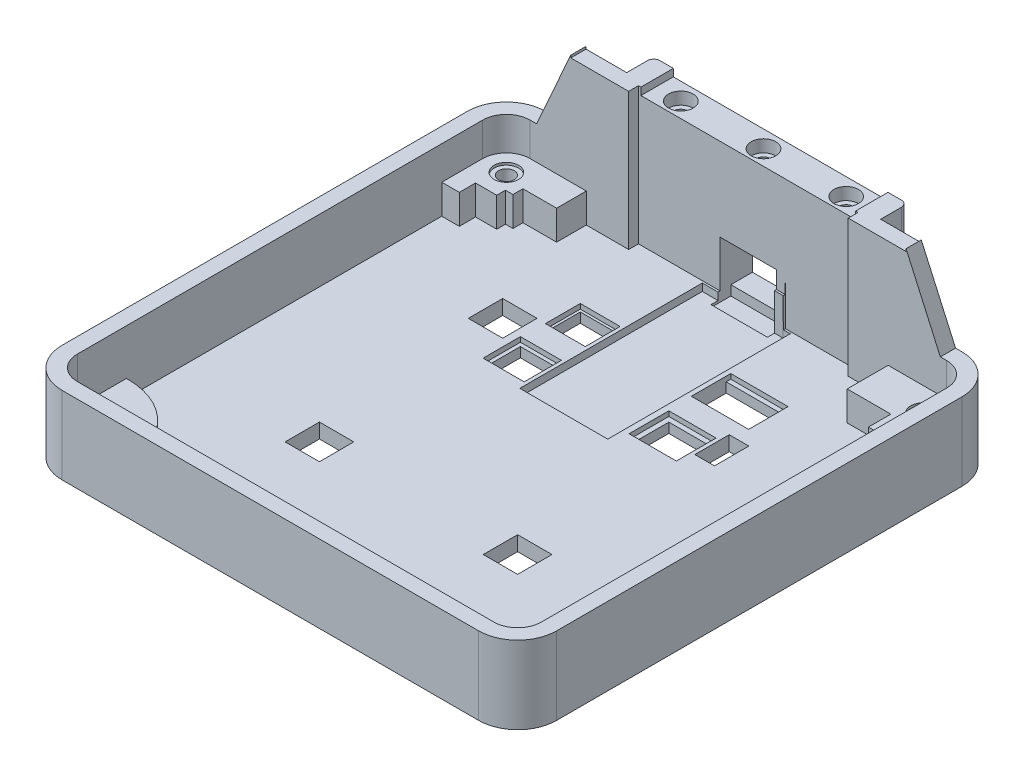
SolidWorks part; units mm, degrees
ref_plane "Front Plane" through (0, 0, 0) normal (0, 0, 1) x (1, 0, 0)
ref_plane "Top Plane" through (0, 0, 0) normal (0, 1, 0) x (1, 0, 0)
ref_plane "Right Plane" through (0, 0, 0) normal (1, 0, 0) x (0, 0, -1)
sketch "Sketch2" plane through (0, 0, 0) normal (0, 1, 0) x (1, 0, 0)
  line L6 (-46.8585, -41.275) -> (-46.8585, 41.275)
  line L8 (46.8585, -41.275) -> (46.8585, 41.275)
  line L9 (42.418, -45.7155) -> (-42.418, -45.7155)
  line L10 (-42.418, 45.7155) -> (-16.8754, 45.7155)
  line L11 (-46.8585, -41.275) -> (-50.3585, -41.275)
  line L14 (-50.3585, -41.275) -> (-50.3585, 41.275)
  line L15 (-42.418, 45.7155) -> (-42.418, 49.2155)
  line L16 (-42.418, 41.275) -> (-37.8452, 38.0373)
  line L17 (-42.418, 49.2155) -> (42.418, 49.2155)
  line L18 (-37.8452, 38.0373) -> (-37.8452, 40.0693)
  line L19 (-37.8452, 40.0693) -> (-30.9872, 40.0693)
  line L20 (-30.9872, 40.0693) -> (-30.9872, 45.7155)
  line L21 (-37.8452, 38.0373) -> (-39.3692, 38.0373)
  line L22 (46.8585, 41.275) -> (50.3585, 41.275)
  line L23 (42.418, -45.7155) -> (42.418, -49.2155)
  line L24 (-39.3692, 38.0373) -> (-39.3692, 36.2593)
  line L25 (42.418, -49.2155) -> (-42.418, -49.2155)
  line L26 (-39.3692, 36.2593) -> (-43.6872, 36.2593)
  line L27 (-43.6872, 36.2593) -> (-43.6872, 32.9573)
  line L28 (50.3585, 41.275) -> (50.3585, -41.275)
  line L34 (-43.6872, 32.9573) -> (-46.8585, 32.9573)
  line L37 (42.418, 41.275) -> (50.0148, 49.9834)
  line L46 (-16.2544, 31.1733) -> (-10.1584, 31.1733)
  line L52 (-10.1584, 31.1733) -> (-10.1584, 25.0773)
  line L58 (-10.1584, 25.0773) -> (-17.2704, 25.0773)
  line L64 (-17.2704, 25.0773) -> (-17.2704, 31.1733)
  line L70 (-17.2704, 31.1733) -> (-16.2544, 31.1733)
  line L76 (-17.2704, 25.0773) -> (-17.2704, 18.9813)
  line L82 (-17.2704, 18.9813) -> (-10.1584, 18.9813)
  line L88 (-10.1584, 18.9813) -> (-10.1584, 12.8853)
  line L94 (-10.1584, 12.8853) -> (-17.2704, 12.8853)
  line L100 (-17.2704, 12.8853) -> (-17.2704, 18.9813)
  line L111 (22.418, 45.7155) -> (42.418, 45.7155)
  line L112 (-10.1584, 31.1733) -> (9.9076, 31.1733)
  line L113 (9.9076, 31.1733) -> (9.9076, 33.7133)
  line L114 (9.9076, 33.7133) -> (20.5756, 33.7133)
  line L115 (20.5756, 33.7133) -> (20.5756, 27.6173)
  line L116 (20.5756, 27.6173) -> (9.9076, 27.6173)
  line L117 (9.9076, 27.6173) -> (9.9076, 31.1733)
  line L118 (9.9076, 27.6173) -> (9.9076, 20.7633)
  line L119 (9.9076, 20.7633) -> (18.7976, 20.7633)
  line L120 (18.7976, 20.7633) -> (18.7976, 14.6673)
  line L121 (18.7976, 14.6673) -> (11.1776, 14.6673)
  line L122 (11.1776, 14.6673) -> (11.1776, 20.7633)
  line L123 (42.418, 41.275) -> (0, 41.275)
  line L124 (42.418, 41.275) -> (39.3704, 37.7815)
  line L125 (39.3704, 37.7815) -> (39.3704, 33.2095)
  line L126 (39.3704, 37.7815) -> (30.4804, 37.7815)
  line L127 (30.4804, 37.7815) -> (30.4804, 45.7155)
  line L128 (39.3704, 33.2095) -> (46.8585, 33.2095)
  line L129 (22.418, 45.7155) -> (-16.8754, 45.7155)
  line L130 (46.8585, -41.275) -> (46.8585, -31.275)
  line L131 (42.418, -45.7155) -> (32.418, -45.7155)
  line L132 (-42.418, -45.7155) -> (-32.418, -45.7155)
  line L133 (-46.8585, -41.275) -> (-46.8585, -31.275)
  arc A0 (-42.418, 45.7155) -> (-46.8585, 41.275) centre (-42.418, 41.275) ccw
  arc A1 (42.418, 45.7155) -> (46.8585, 41.275) centre (42.418, 41.275) cw
  arc A2 (-46.8585, -41.275) -> (-42.418, -45.7155) centre (-42.418, -41.275) ccw
  arc A3 (46.8585, -41.275) -> (42.418, -45.7155) centre (42.418, -41.275) cw
  circle A4 centre (42.418, 41.275) radius 1.6
  circle A5 centre (-42.418, 41.275) radius 1.6
  circle A6 centre (-42.418, -41.275) radius 1.6
  circle A7 centre (42.418, -41.275) radius 1.6
  arc A8 (-42.418, 49.2155) -> (-50.3585, 41.275) centre (-42.418, 41.275) ccw
  arc A9 (42.418, 49.2155) -> (50.3585, 41.275) centre (42.418, 41.275) cw
  arc A10 (42.418, -49.2155) -> (50.3585, -41.275) centre (42.418, -41.275) ccw
  arc A11 (-42.418, -49.2155) -> (-50.3585, -41.275) centre (-42.418, -41.275) cw
  arc A12 (46.8585, -31.275) -> (32.418, -45.7155) centre (46.8585, -45.7155) ccw
  arc A13 (-46.8585, -31.275) -> (-32.418, -45.7155) centre (-46.8585, -45.7155) cw
extrude "Boss-Extrude1" add sketch "Sketch2" along normal blind 3.5 contours L8 A12 L9 A3 A7 | A13 L6 A2 L9 A6 region at (-40.4967, 0, 39.3537) region at (40.4967, 0, 39.3537)
sketch "Sketch5" plane through (0, 0, 0) normal (0, -1, 0) x (1, 0, 0)
  line L0 (-17.2704, -25.0773) -> (-17.2704, -18.9813) construction
  line L1 (42.418, -41.275) -> (50.0148, -49.9834) construction
  line L2 (42.418, -41.275) -> (0, -41.275) construction
  line L3 (42.418, -41.275) -> (39.3704, -37.7815) construction
  line L4 (-42.418, -41.275) -> (-37.8452, -38.0373) construction
  line L5 (-42.418, -45.7155) -> (-16.8754, -45.7155) construction
  line L6 (22.418, -45.7155) -> (-16.8754, -45.7155) construction
  line L7 (22.418, -45.7155) -> (42.418, -45.7155) construction
  line L8 (-42.418, -45.7155) -> (-42.418, -49.2155) construction
  line L9 (-46.8585, 41.275) -> (-46.8585, -41.275) construction
  line L10 (42.418, 45.7155) -> (-42.418, 45.7155) construction
  line L11 (-42.418, 45.7155) -> (-32.418, 45.7155) construction
  line L12 (-46.8585, 41.275) -> (-46.8585, 31.275) construction
  line L13 (42.418, 45.7155) -> (42.418, 49.2155) construction
  line L14 (46.8585, 41.275) -> (46.8585, 31.275) construction
  line L15 (42.418, 45.7155) -> (32.418, 45.7155) construction
  line L16 (46.8585, 41.275) -> (46.8585, -41.275) construction
  line L17 (46.8585, -41.275) -> (50.3585, -41.275) construction
  line L18 (-46.8585, 41.275) -> (-50.3585, 41.275) construction
  line L19 (-37.8452, -38.0373) -> (-39.3692, -38.0373) construction
  line L20 (-39.3692, -38.0373) -> (-39.3692, -36.2593) construction
  line L21 (-39.3692, -36.2593) -> (-43.6872, -36.2593) construction
  line L22 (-43.6872, -36.2593) -> (-43.6872, -32.9573) construction
  line L23 (-43.6872, -32.9573) -> (-46.8585, -32.9573) construction
  line L24 (-37.8452, -38.0373) -> (-37.8452, -40.0693) construction
  line L25 (-37.8452, -40.0693) -> (-30.9872, -40.0693) construction
  line L26 (-30.9872, -40.0693) -> (-30.9872, -45.7155) construction
  line L27 (-42.418, -49.2155) -> (42.418, -49.2155) construction
  line L28 (-50.3585, 41.275) -> (-50.3585, -41.275) construction
  line L29 (42.418, 49.2155) -> (-42.418, 49.2155) construction
  line L30 (9.9076, -31.1733) -> (9.9076, -33.7133) construction
  line L31 (9.9076, -33.7133) -> (20.5756, -33.7133) construction
  line L32 (20.5756, -33.7133) -> (20.5756, -27.6173) construction
  line L33 (20.5756, -27.6173) -> (9.9076, -27.6173) construction
  line L34 (9.9076, -27.6173) -> (9.9076, -31.1733) construction
  line L35 (9.9076, -27.6173) -> (9.9076, -20.7633) construction
  line L36 (9.9076, -20.7633) -> (18.7976, -20.7633) construction
  line L37 (18.7976, -20.7633) -> (18.7976, -14.6673) construction
  line L38 (18.7976, -14.6673) -> (11.1776, -14.6673) construction
  line L39 (11.1776, -14.6673) -> (11.1776, -20.7633) construction
  line L40 (-10.1584, -31.1733) -> (9.9076, -31.1733) construction
  line L41 (50.3585, -41.275) -> (50.3585, 41.275) construction
  line L42 (39.3704, -37.7815) -> (39.3704, -33.2095) construction
  line L43 (39.3704, -33.2095) -> (46.8585, -33.2095) construction
  line L44 (39.3704, -37.7815) -> (30.4804, -37.7815) construction
  line L45 (30.4804, -37.7815) -> (30.4804, -45.7155) construction
  line L46 (-10.1584, -31.1733) -> (-10.1584, -25.0773) construction
  line L47 (-10.1584, -25.0773) -> (-17.2704, -25.0773) construction
  line L48 (-16.2544, -31.1733) -> (-10.1584, -31.1733) construction
  line L49 (-17.2704, -31.1733) -> (-16.2544, -31.1733) construction
  line L50 (-17.2704, -25.0773) -> (-17.2704, -31.1733) construction
  line L51 (-17.2704, -18.9813) -> (-10.1584, -18.9813) construction
  line L52 (-10.1584, -18.9813) -> (-10.1584, -12.8853) construction
  line L53 (-10.1584, -12.8853) -> (-17.2704, -12.8853) construction
  line L54 (-17.2704, -12.8853) -> (-17.2704, -18.9813) construction
  line L55 (-17.2704, -25.0773) -> (-17.2704, -18.9813)
  line L56 (42.418, -41.275) -> (50.0148, -49.9834)
  line L57 (42.418, -41.275) -> (0, -41.275)
  line L58 (42.418, -41.275) -> (39.3704, -37.7815)
  line L59 (-42.418, -41.275) -> (-37.8452, -38.0373)
  line L60 (-42.418, -45.7155) -> (-16.8754, -45.7155)
  line L61 (22.418, -45.7155) -> (-16.8754, -45.7155)
  line L62 (22.418, -45.7155) -> (42.418, -45.7155)
  line L63 (-42.418, -45.7155) -> (-42.418, -49.2155)
  line L64 (-46.8585, 41.275) -> (-46.8585, -41.275)
  line L65 (42.418, 45.7155) -> (-42.418, 45.7155)
  line L66 (-42.418, 45.7155) -> (-32.418, 45.7155)
  line L67 (-46.8585, 41.275) -> (-46.8585, 31.275)
  line L68 (42.418, 45.7155) -> (42.418, 49.2155)
  line L69 (46.8585, 41.275) -> (46.8585, 31.275)
  line L70 (42.418, 45.7155) -> (32.418, 45.7155)
  line L71 (46.8585, 41.275) -> (46.8585, -41.275)
  line L72 (46.8585, -41.275) -> (50.3585, -41.275)
  line L73 (-46.8585, 41.275) -> (-50.3585, 41.275)
  line L74 (-37.8452, -38.0373) -> (-39.3692, -38.0373)
  line L75 (-39.3692, -38.0373) -> (-39.3692, -36.2593)
  line L76 (-39.3692, -36.2593) -> (-43.6872, -36.2593)
  line L77 (-43.6872, -36.2593) -> (-43.6872, -32.9573)
  line L78 (-43.6872, -32.9573) -> (-46.8585, -32.9573)
  line L79 (-37.8452, -38.0373) -> (-37.8452, -40.0693)
  line L80 (-37.8452, -40.0693) -> (-30.9872, -40.0693)
  line L81 (-30.9872, -40.0693) -> (-30.9872, -45.7155)
  line L82 (-42.418, -49.2155) -> (42.418, -49.2155)
  line L83 (-50.3585, 41.275) -> (-50.3585, -41.275)
  line L84 (42.418, 49.2155) -> (-42.418, 49.2155)
  line L85 (9.9076, -31.1733) -> (9.9076, -33.7133)
  line L86 (9.9076, -33.7133) -> (20.5756, -33.7133)
  line L87 (20.5756, -33.7133) -> (20.5756, -27.6173)
  line L88 (20.5756, -27.6173) -> (9.9076, -27.6173)
  line L89 (9.9076, -27.6173) -> (9.9076, -31.1733)
  line L90 (9.9076, -27.6173) -> (9.9076, -20.7633)
  line L91 (9.9076, -20.7633) -> (18.7976, -20.7633)
  line L92 (18.7976, -20.7633) -> (18.7976, -14.6673)
  line L93 (18.7976, -14.6673) -> (11.1776, -14.6673)
  line L94 (11.1776, -14.6673) -> (11.1776, -20.7633)
  line L95 (-10.1584, -31.1733) -> (9.9076, -31.1733)
  line L96 (50.3585, -41.275) -> (50.3585, 41.275)
  line L97 (39.3704, -37.7815) -> (39.3704, -33.2095)
  line L98 (39.3704, -33.2095) -> (46.8585, -33.2095)
  line L99 (39.3704, -37.7815) -> (30.4804, -37.7815)
  line L100 (30.4804, -37.7815) -> (30.4804, -45.7155)
  line L101 (-10.1584, -31.1733) -> (-10.1584, -25.0773)
  line L102 (-10.1584, -25.0773) -> (-17.2704, -25.0773)
  line L103 (-16.2544, -31.1733) -> (-10.1584, -31.1733)
  line L104 (-17.2704, -31.1733) -> (-16.2544, -31.1733)
  line L105 (-17.2704, -25.0773) -> (-17.2704, -31.1733)
  line L106 (-17.2704, -18.9813) -> (-10.1584, -18.9813)
  line L107 (-10.1584, -18.9813) -> (-10.1584, -12.8853)
  line L108 (-10.1584, -12.8853) -> (-17.2704, -12.8853)
  line L109 (-17.2704, -12.8853) -> (-17.2704, -18.9813)
  line L110 (50.3585, -41.275) -> (50.3585, 41.275)
  line L111 (42.418, 49.2155) -> (-42.418, 49.2155)
  line L112 (-50.3585, 41.275) -> (-50.3585, -41.275)
  line L113 (-42.418, -49.2155) -> (42.418, -49.2155)
  arc A0 (42.418, -45.7155) -> (46.8585, -41.275) centre (42.418, -41.275) ccw construction
  arc A1 (-46.8585, -41.275) -> (-42.418, -45.7155) centre (-42.418, -41.275) ccw construction
  arc A2 (-46.8585, 31.275) -> (-32.418, 45.7155) centre (-46.8585, 45.7155) ccw construction
  arc A3 (-42.418, 45.7155) -> (-46.8585, 41.275) centre (-42.418, 41.275) ccw construction
  arc A4 (32.418, 45.7155) -> (46.8585, 31.275) centre (46.8585, 45.7155) ccw construction
  arc A5 (46.8585, 41.275) -> (42.418, 45.7155) centre (42.418, 41.275) ccw construction
  arc A6 (42.418, -49.2155) -> (50.3585, -41.275) centre (42.418, -41.275) ccw construction
  arc A7 (-50.3585, -41.275) -> (-42.418, -49.2155) centre (-42.418, -41.275) ccw construction
  arc A8 (-42.418, 49.2155) -> (-50.3585, 41.275) centre (-42.418, 41.275) ccw construction
  arc A9 (50.3585, 41.275) -> (42.418, 49.2155) centre (42.418, 41.275) ccw construction
  circle A10 centre (42.418, 41.275) radius 1.6 construction
  circle A11 centre (-42.418, 41.275) radius 1.6 construction
  circle A12 centre (-42.418, -41.275) radius 1.6 construction
  circle A13 centre (42.418, -41.275) radius 1.6 construction
  arc A14 (42.418, -45.7155) -> (46.8585, -41.275) centre (42.418, -41.275) ccw
  arc A15 (-46.8585, -41.275) -> (-42.418, -45.7155) centre (-42.418, -41.275) ccw
  arc A16 (-46.8585, 31.275) -> (-32.418, 45.7155) centre (-46.8585, 45.7155) ccw
  arc A17 (-42.418, 45.7155) -> (-46.8585, 41.275) centre (-42.418, 41.275) ccw
  arc A18 (32.418, 45.7155) -> (46.8585, 31.275) centre (46.8585, 45.7155) ccw
  arc A19 (46.8585, 41.275) -> (42.418, 45.7155) centre (42.418, 41.275) ccw
  arc A20 (42.418, -49.2155) -> (50.3585, -41.275) centre (42.418, -41.275) ccw
  arc A21 (-50.3585, -41.275) -> (-42.418, -49.2155) centre (-42.418, -41.275) ccw
  arc A22 (-42.418, 49.2155) -> (-50.3585, 41.275) centre (-42.418, 41.275) ccw
  arc A23 (50.3585, 41.275) -> (42.418, 49.2155) centre (42.418, 41.275) ccw
  circle A24 centre (42.418, 41.275) radius 1.6
  circle A25 centre (-42.418, 41.275) radius 1.6
  circle A26 centre (-42.418, -41.275) radius 1.6
  circle A27 centre (42.418, -41.275) radius 1.6
  arc A28 (42.418, -49.2155) -> (50.3585, -41.275) centre (42.418, -41.275) ccw
  arc A29 (50.3585, 41.275) -> (42.418, 49.2155) centre (42.418, 41.275) ccw
  arc A30 (-42.418, 49.2155) -> (-50.3585, 41.275) centre (-42.418, 41.275) ccw
  arc A31 (-50.3585, -41.275) -> (-42.418, -49.2155) centre (-42.418, -41.275) ccw
  arc M1 (-46.8585, 31.275) -> (-32.418, 45.7155) centre (-46.8585, 45.7155) ccw
  line M2 (-32.418, 45.7155) -> (-42.418, 45.7155)
  arc M3 (-42.418, 45.7155) -> (-46.8585, 41.275) centre (-42.418, 41.275) ccw
  line M4 (-46.8585, 41.275) -> (-46.8585, 31.275)
  circle M5 centre (-42.418, 41.275) radius 1.6
extrude "Boss-Extrude3" add sketch "Sketch5" along normal blind 2 contours L82 A20 L56 A14 L62 L61 L60 L63 | L56 A20 L72 A14 | L96 A23 L68 A19 L69 L71 L72 | A18 L65 L64 L78 L77 L76 L75 L74 L79 L80 L81 L60 L61 L62 L100 L99 L97 L98 L71 L109 L108 L107 L106 L102 L101 L89 L94 L93 L92 L91 L88 L87 L86 L85 L103 L104 L105 M1 | A27 L58 L99 L100 L57 | A27 L57 L100 L62 A14 L56 | A27 L56 A14 L71 L98 L97 L58 | A26 L74 L75 L76 L77 L78 L64 A15 L60 L81 L80 L79 | M4 M1 M2 M3 M5 | L69 A19 L65 A18 A24 | L84 A22 L73 L65 L68 M3 M2 | L83 A21 L63 A15 L64 L73 M4 region at (43.6425, 0, -37.4818) region at (37.0258, 0, -43.6304) region at (35.5464, 0, -39.5753) region at (48.0295, 0, -43.8264) region at (2.2185, 0, -47.4473) region at (-0.2178, 0, 0.4927) region at (48.3825, 0, 4.776) region at (-48.3825, 0, -4.776) region at (40.4967, 0, 39.3537) region at (-39.9913, 0, -40.9811) region at (-4.7781, 0, 47.245) region at (-40.4967, 0, 39.3537)
sketch "Sketch6" plane through (0, 0, 0) normal (0, 1, 0) x (1, 0, 0)
  line L0 (-17.2704, 25.0773) -> (-17.2704, 18.9813) construction
  line L1 (42.418, 41.275) -> (50.0148, 49.9834) construction
  line L2 (42.418, 41.275) -> (0, 41.275) construction
  line L3 (42.418, 41.275) -> (39.3704, 37.7815) construction
  line L4 (-42.418, 41.275) -> (-37.8452, 38.0373) construction
  line L5 (-42.418, 45.7155) -> (-16.8754, 45.7155) construction
  line L6 (22.418, 45.7155) -> (-16.8754, 45.7155) construction
  line L7 (22.418, 45.7155) -> (42.418, 45.7155) construction
  line L8 (-42.418, 45.7155) -> (-42.418, 49.2155) construction
  line L9 (-46.8585, -41.275) -> (-46.8585, 41.275) construction
  line L10 (42.418, -45.7155) -> (-42.418, -45.7155) construction
  line L11 (-42.418, -45.7155) -> (-32.418, -45.7155) construction
  line L12 (-46.8585, -41.275) -> (-46.8585, -31.275) construction
  line L13 (42.418, -45.7155) -> (42.418, -49.2155) construction
  line L14 (46.8585, -41.275) -> (46.8585, -31.275) construction
  line L15 (42.418, -45.7155) -> (32.418, -45.7155) construction
  line L16 (46.8585, -41.275) -> (46.8585, 41.275) construction
  line L17 (46.8585, 41.275) -> (50.3585, 41.275) construction
  line L18 (-46.8585, -41.275) -> (-50.3585, -41.275) construction
  line L19 (-37.8452, 38.0373) -> (-39.3692, 38.0373) construction
  line L20 (-39.3692, 38.0373) -> (-39.3692, 36.2593) construction
  line L21 (-39.3692, 36.2593) -> (-43.6872, 36.2593) construction
  line L22 (-43.6872, 36.2593) -> (-43.6872, 32.9573) construction
  line L23 (-43.6872, 32.9573) -> (-46.8585, 32.9573) construction
  line L24 (-37.8452, 38.0373) -> (-37.8452, 40.0693) construction
  line L25 (-37.8452, 40.0693) -> (-30.9872, 40.0693) construction
  line L26 (-30.9872, 40.0693) -> (-30.9872, 45.7155) construction
  line L27 (-42.418, 49.2155) -> (42.418, 49.2155) construction
  line L28 (-50.3585, -41.275) -> (-50.3585, 41.275) construction
  line L29 (42.418, -49.2155) -> (-42.418, -49.2155) construction
  line L30 (9.9076, 31.1733) -> (9.9076, 33.7133) construction
  line L31 (9.9076, 33.7133) -> (20.5756, 33.7133) construction
  line L32 (20.5756, 33.7133) -> (20.5756, 27.6173) construction
  line L33 (20.5756, 27.6173) -> (9.9076, 27.6173) construction
  line L34 (9.9076, 27.6173) -> (9.9076, 31.1733) construction
  line L35 (9.9076, 27.6173) -> (9.9076, 20.7633) construction
  line L36 (9.9076, 20.7633) -> (18.7976, 20.7633) construction
  line L37 (18.7976, 20.7633) -> (18.7976, 14.6673) construction
  line L38 (18.7976, 14.6673) -> (11.1776, 14.6673) construction
  line L39 (11.1776, 14.6673) -> (11.1776, 20.7633) construction
  line L40 (-10.1584, 31.1733) -> (9.9076, 31.1733) construction
  line L41 (50.3585, 41.275) -> (50.3585, -41.275) construction
  line L42 (39.3704, 37.7815) -> (39.3704, 33.2095) construction
  line L43 (39.3704, 33.2095) -> (46.8585, 33.2095) construction
  line L44 (39.3704, 37.7815) -> (30.4804, 37.7815) construction
  line L45 (30.4804, 37.7815) -> (30.4804, 45.7155) construction
  line L46 (-10.1584, 31.1733) -> (-10.1584, 25.0773) construction
  line L47 (-10.1584, 25.0773) -> (-17.2704, 25.0773) construction
  line L48 (-16.2544, 31.1733) -> (-10.1584, 31.1733) construction
  line L49 (-17.2704, 31.1733) -> (-16.2544, 31.1733) construction
  line L50 (-17.2704, 25.0773) -> (-17.2704, 31.1733) construction
  line L51 (-17.2704, 18.9813) -> (-10.1584, 18.9813) construction
  line L52 (-10.1584, 18.9813) -> (-10.1584, 12.8853) construction
  line L53 (-10.1584, 12.8853) -> (-17.2704, 12.8853) construction
  line L54 (-17.2704, 12.8853) -> (-17.2704, 18.9813) construction
  line L55 (-17.2704, 25.0773) -> (-17.2704, 18.9813)
  line L56 (42.418, 41.275) -> (50.0148, 49.9834)
  line L57 (42.418, 41.275) -> (0, 41.275)
  line L58 (42.418, 41.275) -> (39.3704, 37.7815)
  line L59 (-42.418, 41.275) -> (-37.8452, 38.0373)
  line L60 (-42.418, 45.7155) -> (-16.8754, 45.7155)
  line L61 (22.418, 45.7155) -> (-16.8754, 45.7155)
  line L62 (22.418, 45.7155) -> (42.418, 45.7155)
  line L63 (-42.418, 45.7155) -> (-42.418, 49.2155)
  line L64 (-46.8585, -41.275) -> (-46.8585, 41.275)
  line L65 (42.418, -45.7155) -> (-42.418, -45.7155)
  line L66 (-42.418, -45.7155) -> (-32.418, -45.7155)
  line L67 (-46.8585, -41.275) -> (-46.8585, -31.275)
  line L68 (42.418, -45.7155) -> (42.418, -49.2155)
  line L69 (46.8585, -41.275) -> (46.8585, -31.275)
  line L70 (42.418, -45.7155) -> (32.418, -45.7155)
  line L71 (46.8585, -41.275) -> (46.8585, 41.275)
  line L72 (46.8585, 41.275) -> (50.3585, 41.275)
  line L73 (-46.8585, -41.275) -> (-50.3585, -41.275)
  line L74 (-37.8452, 38.0373) -> (-39.3692, 38.0373)
  line L75 (-39.3692, 38.0373) -> (-39.3692, 36.2593)
  line L76 (-39.3692, 36.2593) -> (-43.6872, 36.2593)
  line L77 (-43.6872, 36.2593) -> (-43.6872, 32.9573)
  line L78 (-43.6872, 32.9573) -> (-46.8585, 32.9573)
  line L79 (-37.8452, 38.0373) -> (-37.8452, 40.0693)
  line L80 (-37.8452, 40.0693) -> (-30.9872, 40.0693)
  line L81 (-30.9872, 40.0693) -> (-30.9872, 45.7155)
  line L82 (-42.418, 49.2155) -> (42.418, 49.2155)
  line L83 (-50.3585, -41.275) -> (-50.3585, 41.275)
  line L84 (42.418, -49.2155) -> (-42.418, -49.2155)
  line L85 (9.9076, 31.1733) -> (9.9076, 33.7133)
  line L86 (9.9076, 33.7133) -> (20.5756, 33.7133)
  line L87 (20.5756, 33.7133) -> (20.5756, 27.6173)
  line L88 (20.5756, 27.6173) -> (9.9076, 27.6173)
  line L89 (9.9076, 27.6173) -> (9.9076, 31.1733)
  line L90 (9.9076, 27.6173) -> (9.9076, 20.7633)
  line L91 (9.9076, 20.7633) -> (18.7976, 20.7633)
  line L92 (18.7976, 20.7633) -> (18.7976, 14.6673)
  line L93 (18.7976, 14.6673) -> (11.1776, 14.6673)
  line L94 (11.1776, 14.6673) -> (11.1776, 20.7633)
  line L95 (-10.1584, 31.1733) -> (9.9076, 31.1733)
  line L96 (50.3585, 41.275) -> (50.3585, -41.275)
  line L97 (39.3704, 37.7815) -> (39.3704, 33.2095)
  line L98 (39.3704, 33.2095) -> (46.8585, 33.2095)
  line L99 (39.3704, 37.7815) -> (30.4804, 37.7815)
  line L100 (30.4804, 37.7815) -> (30.4804, 45.7155)
  line L101 (-10.1584, 31.1733) -> (-10.1584, 25.0773)
  line L102 (-10.1584, 25.0773) -> (-17.2704, 25.0773)
  line L103 (-16.2544, 31.1733) -> (-10.1584, 31.1733)
  line L104 (-17.2704, 31.1733) -> (-16.2544, 31.1733)
  line L105 (-17.2704, 25.0773) -> (-17.2704, 31.1733)
  line L106 (-17.2704, 18.9813) -> (-10.1584, 18.9813)
  line L107 (-10.1584, 18.9813) -> (-10.1584, 12.8853)
  line L108 (-10.1584, 12.8853) -> (-17.2704, 12.8853)
  line L109 (-17.2704, 12.8853) -> (-17.2704, 18.9813)
  line L110 (30.4804, 45.7155) -> (30.4804, 37.7815)
  line L111 (39.3704, 37.7815) -> (39.3704, 33.2095)
  line L112 (30.4804, 37.7815) -> (39.3704, 37.7815)
  line L113 (39.3704, 33.2095) -> (46.8585, 33.2095)
  line L114 (46.8585, 33.2095) -> (46.8585, 41.275)
  line L115 (42.418, 45.7155) -> (30.4804, 45.7155)
  line L116 (-42.418, 45.7155) -> (-30.9872, 45.7155)
  line L117 (-30.9872, 45.7155) -> (-30.9872, 40.0693)
  line L118 (-30.9872, 40.0693) -> (-37.8452, 40.0693)
  line L119 (-37.8452, 40.0693) -> (-37.8452, 38.0373)
  line L120 (-37.8452, 38.0373) -> (-39.3692, 38.0373)
  line L121 (-39.3692, 38.0373) -> (-39.3692, 36.2593)
  line L122 (-39.3692, 36.2593) -> (-43.6872, 36.2593)
  line L123 (-43.6872, 36.2593) -> (-43.6872, 32.9573)
  line L124 (-43.6872, 32.9573) -> (-46.8585, 32.9573)
  line L125 (-46.8585, 32.9573) -> (-46.8585, 41.275)
  arc A0 (46.8585, 41.275) -> (42.418, 45.7155) centre (42.418, 41.275) ccw construction
  arc A1 (-42.418, 45.7155) -> (-46.8585, 41.275) centre (-42.418, 41.275) ccw construction
  arc A2 (-32.418, -45.7155) -> (-46.8585, -31.275) centre (-46.8585, -45.7155) ccw construction
  arc A3 (-46.8585, -41.275) -> (-42.418, -45.7155) centre (-42.418, -41.275) ccw construction
  arc A4 (46.8585, -31.275) -> (32.418, -45.7155) centre (46.8585, -45.7155) ccw construction
  arc A5 (42.418, -45.7155) -> (46.8585, -41.275) centre (42.418, -41.275) ccw construction
  arc A6 (50.3585, 41.275) -> (42.418, 49.2155) centre (42.418, 41.275) ccw construction
  arc A7 (-42.418, 49.2155) -> (-50.3585, 41.275) centre (-42.418, 41.275) ccw construction
  arc A8 (-50.3585, -41.275) -> (-42.418, -49.2155) centre (-42.418, -41.275) ccw construction
  arc A9 (42.418, -49.2155) -> (50.3585, -41.275) centre (42.418, -41.275) ccw construction
  circle A10 centre (42.418, -41.275) radius 1.6 construction
  circle A11 centre (-42.418, -41.275) radius 1.6 construction
  circle A12 centre (-42.418, 41.275) radius 1.6 construction
  circle A13 centre (42.418, 41.275) radius 1.6 construction
  arc A14 (46.8585, 41.275) -> (42.418, 45.7155) centre (42.418, 41.275) ccw
  arc A15 (-42.418, 45.7155) -> (-46.8585, 41.275) centre (-42.418, 41.275) ccw
  arc A16 (-32.418, -45.7155) -> (-46.8585, -31.275) centre (-46.8585, -45.7155) ccw
  arc A17 (-46.8585, -41.275) -> (-42.418, -45.7155) centre (-42.418, -41.275) ccw
  arc A18 (46.8585, -31.275) -> (32.418, -45.7155) centre (46.8585, -45.7155) ccw
  arc A19 (42.418, -45.7155) -> (46.8585, -41.275) centre (42.418, -41.275) ccw
  arc A20 (50.3585, 41.275) -> (42.418, 49.2155) centre (42.418, 41.275) ccw
  arc A21 (-42.418, 49.2155) -> (-50.3585, 41.275) centre (-42.418, 41.275) ccw
  arc A22 (-50.3585, -41.275) -> (-42.418, -49.2155) centre (-42.418, -41.275) ccw
  arc A23 (42.418, -49.2155) -> (50.3585, -41.275) centre (42.418, -41.275) ccw
  circle A24 centre (42.418, -41.275) radius 1.6
  circle A25 centre (-42.418, -41.275) radius 1.6
  circle A26 centre (-42.418, 41.275) radius 1.6
  circle A27 centre (42.418, 41.275) radius 1.6
  arc A28 (-46.8585, 41.275) -> (-42.418, 45.7155) centre (-42.418, 41.275) cw
  arc A29 (46.8585, 41.275) -> (42.418, 45.7155) centre (42.418, 41.275) ccw
  circle M17 centre (42.418, 41.275) radius 1.6
  circle M34 centre (-42.418, 41.275) radius 1.6
extrude "Boss-Extrude4" add sketch "Sketch6" along normal blind 6 contours L56 A14 L62 L100 L57 M17 | L100 L99 L58 L57 M17 | L71 A14 L56 L58 L97 L98 M17 | L60 A15 L64 L78 L77 L76 L75 L74 L79 L80 L81 M34 region at (37.0258, 0, -43.6304) region at (43.6425, 0, -37.4818) region at (35.5464, 0, -39.5753) region at (-39.9913, 0, -40.9811)
sketch "Sketch7" plane through (0, 0, 0) normal (0, 1, 0) x (1, 0, 0)
  line L0 (-17.2704, 25.0773) -> (-17.2704, 18.9813) construction
  line L1 (42.418, 41.275) -> (50.0148, 49.9834) construction
  line L2 (42.418, 41.275) -> (0, 41.275) construction
  line L3 (42.418, 41.275) -> (39.3704, 37.7815) construction
  line L4 (-42.418, 41.275) -> (-37.8452, 38.0373) construction
  line L5 (-42.418, 45.7155) -> (-16.8754, 45.7155) construction
  line L6 (22.418, 45.7155) -> (-16.8754, 45.7155) construction
  line L7 (22.418, 45.7155) -> (42.418, 45.7155) construction
  line L8 (-42.418, 45.7155) -> (-42.418, 49.2155) construction
  line L9 (-46.8585, -41.275) -> (-46.8585, 41.275) construction
  line L10 (42.418, -45.7155) -> (-42.418, -45.7155) construction
  line L11 (-42.418, -45.7155) -> (-32.418, -45.7155) construction
  line L12 (-46.8585, -41.275) -> (-46.8585, -31.275) construction
  line L13 (42.418, -45.7155) -> (42.418, -49.2155) construction
  line L14 (46.8585, -41.275) -> (46.8585, -31.275) construction
  line L15 (42.418, -45.7155) -> (32.418, -45.7155) construction
  line L16 (46.8585, -41.275) -> (46.8585, 41.275) construction
  line L17 (46.8585, 41.275) -> (50.3585, 41.275) construction
  line L18 (-46.8585, -41.275) -> (-50.3585, -41.275) construction
  line L19 (-37.8452, 38.0373) -> (-39.3692, 38.0373) construction
  line L20 (-39.3692, 38.0373) -> (-39.3692, 36.2593) construction
  line L21 (-39.3692, 36.2593) -> (-43.6872, 36.2593) construction
  line L22 (-43.6872, 36.2593) -> (-43.6872, 32.9573) construction
  line L23 (-43.6872, 32.9573) -> (-46.8585, 32.9573) construction
  line L24 (-37.8452, 38.0373) -> (-37.8452, 40.0693) construction
  line L25 (-37.8452, 40.0693) -> (-30.9872, 40.0693) construction
  line L26 (-30.9872, 40.0693) -> (-30.9872, 45.7155) construction
  line L27 (-42.418, 49.2155) -> (42.418, 49.2155) construction
  line L28 (-50.3585, -41.275) -> (-50.3585, 41.275) construction
  line L29 (42.418, -49.2155) -> (-42.418, -49.2155) construction
  line L30 (9.9076, 31.1733) -> (9.9076, 33.7133) construction
  line L31 (9.9076, 33.7133) -> (20.5756, 33.7133) construction
  line L32 (20.5756, 33.7133) -> (20.5756, 27.6173) construction
  line L33 (20.5756, 27.6173) -> (9.9076, 27.6173) construction
  line L34 (9.9076, 27.6173) -> (9.9076, 31.1733) construction
  line L35 (9.9076, 27.6173) -> (9.9076, 20.7633) construction
  line L36 (9.9076, 20.7633) -> (18.7976, 20.7633) construction
  line L37 (18.7976, 20.7633) -> (18.7976, 14.6673) construction
  line L38 (18.7976, 14.6673) -> (11.1776, 14.6673) construction
  line L39 (11.1776, 14.6673) -> (11.1776, 20.7633) construction
  line L40 (-10.1584, 31.1733) -> (9.9076, 31.1733) construction
  line L41 (50.3585, 41.275) -> (50.3585, -41.275) construction
  line L42 (39.3704, 37.7815) -> (39.3704, 33.2095) construction
  line L43 (39.3704, 33.2095) -> (46.8585, 33.2095) construction
  line L44 (39.3704, 37.7815) -> (30.4804, 37.7815) construction
  line L45 (30.4804, 37.7815) -> (30.4804, 45.7155) construction
  line L46 (-10.1584, 31.1733) -> (-10.1584, 25.0773) construction
  line L47 (-10.1584, 25.0773) -> (-17.2704, 25.0773) construction
  line L48 (-16.2544, 31.1733) -> (-10.1584, 31.1733) construction
  line L49 (-17.2704, 31.1733) -> (-16.2544, 31.1733) construction
  line L50 (-17.2704, 25.0773) -> (-17.2704, 31.1733) construction
  line L51 (-17.2704, 18.9813) -> (-10.1584, 18.9813) construction
  line L52 (-10.1584, 18.9813) -> (-10.1584, 12.8853) construction
  line L53 (-10.1584, 12.8853) -> (-17.2704, 12.8853) construction
  line L54 (-17.2704, 12.8853) -> (-17.2704, 18.9813) construction
  line L55 (-17.2704, 25.0773) -> (-17.2704, 18.9813)
  line L56 (42.418, 41.275) -> (50.0148, 49.9834)
  line L57 (42.418, 41.275) -> (0, 41.275)
  line L58 (42.418, 41.275) -> (39.3704, 37.7815)
  line L59 (-42.418, 41.275) -> (-37.8452, 38.0373)
  line L60 (-42.418, 45.7155) -> (-16.8754, 45.7155)
  line L61 (22.418, 45.7155) -> (-16.8754, 45.7155)
  line L62 (22.418, 45.7155) -> (42.418, 45.7155)
  line L63 (-42.418, 45.7155) -> (-42.418, 49.2155)
  line L64 (-46.8585, -41.275) -> (-46.8585, 41.275)
  line L65 (42.418, -45.7155) -> (-42.418, -45.7155)
  line L66 (-42.418, -45.7155) -> (-32.418, -45.7155)
  line L67 (-46.8585, -41.275) -> (-46.8585, -31.275)
  line L68 (42.418, -45.7155) -> (42.418, -49.2155)
  line L69 (46.8585, -41.275) -> (46.8585, -31.275)
  line L70 (42.418, -45.7155) -> (32.418, -45.7155)
  line L71 (46.8585, -41.275) -> (46.8585, 41.275)
  line L72 (46.8585, 41.275) -> (50.3585, 41.275)
  line L73 (-46.8585, -41.275) -> (-50.3585, -41.275)
  line L74 (-37.8452, 38.0373) -> (-39.3692, 38.0373)
  line L75 (-39.3692, 38.0373) -> (-39.3692, 36.2593)
  line L76 (-39.3692, 36.2593) -> (-43.6872, 36.2593)
  line L77 (-43.6872, 36.2593) -> (-43.6872, 32.9573)
  line L78 (-43.6872, 32.9573) -> (-46.8585, 32.9573)
  line L79 (-37.8452, 38.0373) -> (-37.8452, 40.0693)
  line L80 (-37.8452, 40.0693) -> (-30.9872, 40.0693)
  line L81 (-30.9872, 40.0693) -> (-30.9872, 45.7155)
  line L82 (-42.418, 49.2155) -> (42.418, 49.2155)
  line L83 (-50.3585, -41.275) -> (-50.3585, 41.275)
  line L84 (42.418, -49.2155) -> (-42.418, -49.2155)
  line L85 (9.9076, 31.1733) -> (9.9076, 33.7133)
  line L86 (9.9076, 33.7133) -> (20.5756, 33.7133)
  line L87 (20.5756, 33.7133) -> (20.5756, 27.6173)
  line L88 (20.5756, 27.6173) -> (9.9076, 27.6173)
  line L89 (9.9076, 27.6173) -> (9.9076, 31.1733)
  line L90 (9.9076, 27.6173) -> (9.9076, 20.7633)
  line L91 (9.9076, 20.7633) -> (18.7976, 20.7633)
  line L92 (18.7976, 20.7633) -> (18.7976, 14.6673)
  line L93 (18.7976, 14.6673) -> (11.1776, 14.6673)
  line L94 (11.1776, 14.6673) -> (11.1776, 20.7633)
  line L95 (-10.1584, 31.1733) -> (9.9076, 31.1733)
  line L96 (50.3585, 41.275) -> (50.3585, -41.275)
  line L97 (39.3704, 37.7815) -> (39.3704, 33.2095)
  line L98 (39.3704, 33.2095) -> (46.8585, 33.2095)
  line L99 (39.3704, 37.7815) -> (30.4804, 37.7815)
  line L100 (30.4804, 37.7815) -> (30.4804, 45.7155)
  line L101 (-10.1584, 31.1733) -> (-10.1584, 25.0773)
  line L102 (-10.1584, 25.0773) -> (-17.2704, 25.0773)
  line L103 (-16.2544, 31.1733) -> (-10.1584, 31.1733)
  line L104 (-17.2704, 31.1733) -> (-16.2544, 31.1733)
  line L105 (-17.2704, 25.0773) -> (-17.2704, 31.1733)
  line L106 (-17.2704, 18.9813) -> (-10.1584, 18.9813)
  line L107 (-10.1584, 18.9813) -> (-10.1584, 12.8853)
  line L108 (-10.1584, 12.8853) -> (-17.2704, 12.8853)
  line L109 (-17.2704, 12.8853) -> (-17.2704, 18.9813)
  line L110 (0, 41.275) -> (-7.5, 41.275)
  line L111 (0, 41.275) -> (7.5, 41.275)
  line L112 (7.5, 41.275) -> (7.5, 49.2155)
  line L113 (-7.5, 41.275) -> (-7.5, 49.2155)
  arc A0 (46.8585, 41.275) -> (42.418, 45.7155) centre (42.418, 41.275) ccw construction
  arc A1 (-42.418, 45.7155) -> (-46.8585, 41.275) centre (-42.418, 41.275) ccw construction
  arc A2 (-32.418, -45.7155) -> (-46.8585, -31.275) centre (-46.8585, -45.7155) ccw construction
  arc A3 (-46.8585, -41.275) -> (-42.418, -45.7155) centre (-42.418, -41.275) ccw construction
  arc A4 (46.8585, -31.275) -> (32.418, -45.7155) centre (46.8585, -45.7155) ccw construction
  arc A5 (42.418, -45.7155) -> (46.8585, -41.275) centre (42.418, -41.275) ccw construction
  arc A6 (50.3585, 41.275) -> (42.418, 49.2155) centre (42.418, 41.275) ccw construction
  arc A7 (-42.418, 49.2155) -> (-50.3585, 41.275) centre (-42.418, 41.275) ccw construction
  arc A8 (-50.3585, -41.275) -> (-42.418, -49.2155) centre (-42.418, -41.275) ccw construction
  arc A9 (42.418, -49.2155) -> (50.3585, -41.275) centre (42.418, -41.275) ccw construction
  circle A10 centre (42.418, -41.275) radius 1.6 construction
  circle A11 centre (-42.418, -41.275) radius 1.6 construction
  circle A12 centre (-42.418, 41.275) radius 1.6 construction
  circle A13 centre (42.418, 41.275) radius 1.6 construction
  arc A14 (46.8585, 41.275) -> (42.418, 45.7155) centre (42.418, 41.275) ccw
  arc A15 (-42.418, 45.7155) -> (-46.8585, 41.275) centre (-42.418, 41.275) ccw
  arc A16 (-32.418, -45.7155) -> (-46.8585, -31.275) centre (-46.8585, -45.7155) ccw
  arc A17 (-46.8585, -41.275) -> (-42.418, -45.7155) centre (-42.418, -41.275) ccw
  arc A18 (46.8585, -31.275) -> (32.418, -45.7155) centre (46.8585, -45.7155) ccw
  arc A19 (42.418, -45.7155) -> (46.8585, -41.275) centre (42.418, -41.275) ccw
  arc A20 (50.3585, 41.275) -> (42.418, 49.2155) centre (42.418, 41.275) ccw
  arc A21 (-42.418, 49.2155) -> (-50.3585, 41.275) centre (-42.418, 41.275) ccw
  arc A22 (-50.3585, -41.275) -> (-42.418, -49.2155) centre (-42.418, -41.275) ccw
  arc A23 (42.418, -49.2155) -> (50.3585, -41.275) centre (42.418, -41.275) ccw
  circle A24 centre (42.418, -41.275) radius 1.6
  circle A25 centre (-42.418, -41.275) radius 1.6
  circle A26 centre (-42.418, 41.275) radius 1.6
  circle A27 centre (42.418, 41.275) radius 1.6
extrude "Cut-Extrude1" cut sketch "Sketch7" against normal blind 18.7 contours L113 L61 L112 L82 | L113 L110 L57 L112 L61 region at (0, 0, -43.4953) region at (0, 0, -47.4655)
sketch "Sketch8" plane through (0, 0, 0) normal (0, 1, 0) x (1, 0, 0)
  line L0 (-17.2704, 25.0773) -> (-17.2704, 18.9813) construction
  line L1 (42.418, 41.275) -> (50.0148, 49.9834) construction
  line L2 (42.418, 41.275) -> (0, 41.275) construction
  line L3 (42.418, 41.275) -> (39.3704, 37.7815) construction
  line L4 (-42.418, 41.275) -> (-37.8452, 38.0373) construction
  line L5 (-42.418, 45.7155) -> (-16.8754, 45.7155) construction
  line L6 (22.418, 45.7155) -> (-16.8754, 45.7155) construction
  line L7 (22.418, 45.7155) -> (42.418, 45.7155) construction
  line L8 (-42.418, 45.7155) -> (-42.418, 49.2155) construction
  line L9 (-46.8585, -41.275) -> (-46.8585, 41.275) construction
  line L10 (42.418, -45.7155) -> (-42.418, -45.7155) construction
  line L11 (-42.418, -45.7155) -> (-32.418, -45.7155) construction
  line L12 (-46.8585, -41.275) -> (-46.8585, -31.275) construction
  line L13 (42.418, -45.7155) -> (42.418, -49.2155) construction
  line L14 (46.8585, -41.275) -> (46.8585, -31.275) construction
  line L15 (42.418, -45.7155) -> (32.418, -45.7155) construction
  line L16 (46.8585, -41.275) -> (46.8585, 41.275) construction
  line L17 (46.8585, 41.275) -> (50.3585, 41.275) construction
  line L18 (-46.8585, -41.275) -> (-50.3585, -41.275) construction
  line L19 (-37.8452, 38.0373) -> (-39.3692, 38.0373) construction
  line L20 (-39.3692, 38.0373) -> (-39.3692, 36.2593) construction
  line L21 (-39.3692, 36.2593) -> (-43.6872, 36.2593) construction
  line L22 (-43.6872, 36.2593) -> (-43.6872, 32.9573) construction
  line L23 (-43.6872, 32.9573) -> (-46.8585, 32.9573) construction
  line L24 (-37.8452, 38.0373) -> (-37.8452, 40.0693) construction
  line L25 (-37.8452, 40.0693) -> (-30.9872, 40.0693) construction
  line L26 (-30.9872, 40.0693) -> (-30.9872, 45.7155) construction
  line L27 (-42.418, 49.2155) -> (42.418, 49.2155) construction
  line L28 (-50.3585, -41.275) -> (-50.3585, 41.275) construction
  line L29 (42.418, -49.2155) -> (-42.418, -49.2155) construction
  line L30 (9.9076, 31.1733) -> (9.9076, 33.7133) construction
  line L31 (9.9076, 33.7133) -> (20.5756, 33.7133) construction
  line L32 (20.5756, 33.7133) -> (20.5756, 27.6173) construction
  line L33 (20.5756, 27.6173) -> (9.9076, 27.6173) construction
  line L34 (9.9076, 27.6173) -> (9.9076, 31.1733) construction
  line L35 (9.9076, 27.6173) -> (9.9076, 20.7633) construction
  line L36 (9.9076, 20.7633) -> (18.7976, 20.7633) construction
  line L37 (18.7976, 20.7633) -> (18.7976, 14.6673) construction
  line L38 (18.7976, 14.6673) -> (11.1776, 14.6673) construction
  line L39 (11.1776, 14.6673) -> (11.1776, 20.7633) construction
  line L40 (-10.1584, 31.1733) -> (9.9076, 31.1733) construction
  line L41 (50.3585, 41.275) -> (50.3585, -41.275) construction
  line L42 (39.3704, 37.7815) -> (39.3704, 33.2095) construction
  line L43 (39.3704, 33.2095) -> (46.8585, 33.2095) construction
  line L44 (39.3704, 37.7815) -> (30.4804, 37.7815) construction
  line L45 (30.4804, 37.7815) -> (30.4804, 45.7155) construction
  line L46 (-10.1584, 31.1733) -> (-10.1584, 25.0773) construction
  line L47 (-10.1584, 25.0773) -> (-17.2704, 25.0773) construction
  line L48 (-16.2544, 31.1733) -> (-10.1584, 31.1733) construction
  line L49 (-17.2704, 31.1733) -> (-16.2544, 31.1733) construction
  line L50 (-17.2704, 25.0773) -> (-17.2704, 31.1733) construction
  line L51 (-17.2704, 18.9813) -> (-10.1584, 18.9813) construction
  line L52 (-10.1584, 18.9813) -> (-10.1584, 12.8853) construction
  line L53 (-10.1584, 12.8853) -> (-17.2704, 12.8853) construction
  line L54 (-17.2704, 12.8853) -> (-17.2704, 18.9813) construction
  line L55 (-17.2704, 25.0773) -> (-17.2704, 18.9813)
  line L56 (42.418, 41.275) -> (50.0148, 49.9834)
  line L57 (42.418, 41.275) -> (0, 41.275)
  line L58 (42.418, 41.275) -> (39.3704, 37.7815)
  line L59 (-42.418, 41.275) -> (-37.8452, 38.0373)
  line L60 (-42.418, 45.7155) -> (-16.8754, 45.7155)
  line L61 (22.418, 45.7155) -> (-16.8754, 45.7155)
  line L62 (22.418, 45.7155) -> (42.418, 45.7155)
  line L63 (-42.418, 45.7155) -> (-42.418, 49.2155)
  line L64 (-46.8585, -41.275) -> (-46.8585, 41.275)
  line L65 (42.418, -45.7155) -> (-42.418, -45.7155)
  line L66 (-42.418, -45.7155) -> (-32.418, -45.7155)
  line L67 (-46.8585, -41.275) -> (-46.8585, -31.275)
  line L68 (42.418, -45.7155) -> (42.418, -49.2155)
  line L69 (46.8585, -41.275) -> (46.8585, -31.275)
  line L70 (42.418, -45.7155) -> (32.418, -45.7155)
  line L71 (46.8585, -41.275) -> (46.8585, 41.275)
  line L72 (46.8585, 41.275) -> (50.3585, 41.275)
  line L73 (-46.8585, -41.275) -> (-50.3585, -41.275)
  line L74 (-37.8452, 38.0373) -> (-39.3692, 38.0373)
  line L75 (-39.3692, 38.0373) -> (-39.3692, 36.2593)
  line L76 (-39.3692, 36.2593) -> (-43.6872, 36.2593)
  line L77 (-43.6872, 36.2593) -> (-43.6872, 32.9573)
  line L78 (-43.6872, 32.9573) -> (-46.8585, 32.9573)
  line L79 (-37.8452, 38.0373) -> (-37.8452, 40.0693)
  line L80 (-37.8452, 40.0693) -> (-30.9872, 40.0693)
  line L81 (-30.9872, 40.0693) -> (-30.9872, 45.7155)
  line L82 (-42.418, 49.2155) -> (42.418, 49.2155)
  line L83 (-50.3585, -41.275) -> (-50.3585, 41.275)
  line L84 (42.418, -49.2155) -> (-42.418, -49.2155)
  line L85 (9.9076, 31.1733) -> (9.9076, 33.7133)
  line L86 (9.9076, 33.7133) -> (20.5756, 33.7133)
  line L87 (20.5756, 33.7133) -> (20.5756, 27.6173)
  line L88 (20.5756, 27.6173) -> (9.9076, 27.6173)
  line L89 (9.9076, 27.6173) -> (9.9076, 31.1733)
  line L90 (9.9076, 27.6173) -> (9.9076, 20.7633)
  line L91 (9.9076, 20.7633) -> (18.7976, 20.7633)
  line L92 (18.7976, 20.7633) -> (18.7976, 14.6673)
  line L93 (18.7976, 14.6673) -> (11.1776, 14.6673)
  line L94 (11.1776, 14.6673) -> (11.1776, 20.7633)
  line L95 (-10.1584, 31.1733) -> (9.9076, 31.1733)
  line L96 (50.3585, 41.275) -> (50.3585, -41.275)
  line L97 (39.3704, 37.7815) -> (39.3704, 33.2095)
  line L98 (39.3704, 33.2095) -> (46.8585, 33.2095)
  line L99 (39.3704, 37.7815) -> (30.4804, 37.7815)
  line L100 (30.4804, 37.7815) -> (30.4804, 45.7155)
  line L101 (-10.1584, 31.1733) -> (-10.1584, 25.0773)
  line L102 (-10.1584, 25.0773) -> (-17.2704, 25.0773)
  line L103 (-16.2544, 31.1733) -> (-10.1584, 31.1733)
  line L104 (-17.2704, 31.1733) -> (-16.2544, 31.1733)
  line L105 (-17.2704, 25.0773) -> (-17.2704, 31.1733)
  line L106 (-17.2704, 18.9813) -> (-10.1584, 18.9813)
  line L107 (-10.1584, 18.9813) -> (-10.1584, 12.8853)
  line L108 (-10.1584, 12.8853) -> (-17.2704, 12.8853)
  line L109 (-17.2704, 12.8853) -> (-17.2704, 18.9813)
  line L110 (-50.3585, -41.275) -> (-50.3585, 41.275)
  line L111 (-42.418, -49.2155) -> (42.418, -49.2155)
  line L112 (50.3585, -41.275) -> (50.3585, 41.275)
  line L113 (42.418, 49.2155) -> (-42.418, 49.2155)
  line L114 (-50.3585, 41.275) -> (-50.3585, -41.275)
  line L115 (-42.418, -45.7155) -> (42.418, -45.7155)
  line L116 (46.8585, -41.275) -> (46.8585, 41.275)
  line L117 (42.418, 45.7155) -> (-42.418, 45.7155)
  line L118 (-46.8585, 41.275) -> (-46.8585, -41.275)
  arc A0 (46.8585, 41.275) -> (42.418, 45.7155) centre (42.418, 41.275) ccw construction
  arc A1 (-42.418, 45.7155) -> (-46.8585, 41.275) centre (-42.418, 41.275) ccw construction
  arc A2 (-32.418, -45.7155) -> (-46.8585, -31.275) centre (-46.8585, -45.7155) ccw construction
  arc A3 (-46.8585, -41.275) -> (-42.418, -45.7155) centre (-42.418, -41.275) ccw construction
  arc A4 (46.8585, -31.275) -> (32.418, -45.7155) centre (46.8585, -45.7155) ccw construction
  arc A5 (42.418, -45.7155) -> (46.8585, -41.275) centre (42.418, -41.275) ccw construction
  arc A6 (50.3585, 41.275) -> (42.418, 49.2155) centre (42.418, 41.275) ccw construction
  arc A7 (-42.418, 49.2155) -> (-50.3585, 41.275) centre (-42.418, 41.275) ccw construction
  arc A8 (-50.3585, -41.275) -> (-42.418, -49.2155) centre (-42.418, -41.275) ccw construction
  arc A9 (42.418, -49.2155) -> (50.3585, -41.275) centre (42.418, -41.275) ccw construction
  circle A10 centre (42.418, -41.275) radius 1.6 construction
  circle A11 centre (-42.418, -41.275) radius 1.6 construction
  circle A12 centre (-42.418, 41.275) radius 1.6 construction
  circle A13 centre (42.418, 41.275) radius 1.6 construction
  arc A14 (46.8585, 41.275) -> (42.418, 45.7155) centre (42.418, 41.275) ccw
  arc A15 (-42.418, 45.7155) -> (-46.8585, 41.275) centre (-42.418, 41.275) ccw
  arc A16 (-32.418, -45.7155) -> (-46.8585, -31.275) centre (-46.8585, -45.7155) ccw
  arc A17 (-46.8585, -41.275) -> (-42.418, -45.7155) centre (-42.418, -41.275) ccw
  arc A18 (46.8585, -31.275) -> (32.418, -45.7155) centre (46.8585, -45.7155) ccw
  arc A19 (42.418, -45.7155) -> (46.8585, -41.275) centre (42.418, -41.275) ccw
  arc A20 (50.3585, 41.275) -> (42.418, 49.2155) centre (42.418, 41.275) ccw
  arc A21 (-42.418, 49.2155) -> (-50.3585, 41.275) centre (-42.418, 41.275) ccw
  arc A22 (-50.3585, -41.275) -> (-42.418, -49.2155) centre (-42.418, -41.275) ccw
  arc A23 (42.418, -49.2155) -> (50.3585, -41.275) centre (42.418, -41.275) ccw
  circle A24 centre (42.418, -41.275) radius 1.6
  circle A25 centre (-42.418, -41.275) radius 1.6
  circle A26 centre (-42.418, 41.275) radius 1.6
  circle A27 centre (42.418, 41.275) radius 1.6
  arc A28 (-46.8585, -41.275) -> (-42.418, -45.7155) centre (-42.418, -41.275) ccw
  arc A29 (42.418, -45.7155) -> (46.8585, -41.275) centre (42.418, -41.275) ccw
  arc A30 (46.8585, 41.275) -> (42.418, 45.7155) centre (42.418, 41.275) ccw
  arc A31 (-42.418, 45.7155) -> (-46.8585, 41.275) centre (-42.418, 41.275) ccw
  arc A32 (-50.3585, -41.275) -> (-42.418, -49.2155) centre (-42.418, -41.275) ccw
  arc A33 (42.418, -49.2155) -> (50.3585, -41.275) centre (42.418, -41.275) ccw
  arc A34 (50.3585, 41.275) -> (42.418, 49.2155) centre (42.418, 41.275) ccw
  arc A35 (-42.418, 49.2155) -> (-50.3585, 41.275) centre (-42.418, 41.275) ccw
extrude "Boss-Extrude5" add sketch "Sketch8" along normal blind 14 contours L63 A21 L83 L73 L64 A15 | L73 A22 L84 L68 L65 A17 | L68 A23 L96 L72 L71 L69 A19 | L56 A20 L82 L63 L60 L61 L62 A14 | L72 A20 L56 A14 region at (2.2185, 0, -47.4473) region at (48.0295, 0, -43.8264) region at (48.3825, 0, 4.776) region at (-48.3825, 0, -4.776) region at (-4.7781, 0, 47.245)
sketch "Sketch10" plane through (0, 6, 0) normal (0, 1, 0) x (1, 0, 0)
  line L0 (-2.3026, 25.6216) -> (-2.3026, 13.0008)
  line L1 (-2.3026, 13.0008) -> (6.3735, 13.0008)
  line L2 (6.3735, 13.0008) -> (6.3735, 25.6216)
  line L3 (6.3735, 25.6216) -> (-2.3026, 25.6216)
extrude "Boss-Extrude6" add sketch "Sketch10" along normal blind 20.2 separate body contours L3 L0 L1 L2
sketch "Sketch11" plane through (0, 0, -49.2155) normal (0, 0, -1) x (-1, 0, 0)
  line L8 (-42.418, -2) -> (-7.5, -2)
  line L9 (-7.5, -2) -> (-7.5, 0)
  line L10 (-7.5, 0) -> (7.5, 0)
  line L11 (7.5, 0) -> (7.5, -2)
  line L12 (7.5, -2) -> (42.418, -2)
  line L13 (42.418, -2) -> (42.418, 14)
  line L14 (42.418, 14) -> (-42.418, 14)
  line L15 (-42.418, 14) -> (-42.418, -2)
  line L16 (-42.418, -2) -> (-7.5, -2)
  line L17 (-7.5, -2) -> (-7.5, 0)
  line L18 (-7.5, 0) -> (7.5, 0)
  line L19 (7.5, 0) -> (7.5, -2)
  line L20 (7.5, -2) -> (42.418, -2)
  line L21 (42.418, -2) -> (42.418, 14)
  line L22 (42.418, 14) -> (-42.418, 14)
  line L23 (-42.418, 14) -> (-42.418, -2)
  dimension "D1" = 0
sketch "Sketch13" plane through (0, -2, 0) normal (0, -1, 0) x (1, 0, 0)
  line L0 (46.8585, -33.2095) -> (46.8585, -68.1275)
  line L1 (-46.8585, -32.9573) -> (-46.8585, -74.0554)
  line L2 (42.418, -49.2155) -> (46.8585, -49.2155)
  line L3 (46.8585, -49.2155) -> (25.8585, -49.2155)
  line L4 (-42.418, -49.2155) -> (42.418, -49.2155) construction
  line L5 (-42.418, -49.2155) -> (-21.418, -49.2155)
  line L6 (-20.1364, -54.7155) -> (24.5769, -54.7155)
  line L7 (25.8585, -53.4339) -> (25.8585, -49.2155)
  line L8 (-20.1364, -54.7155) -> (-24.5769, -54.7155)
  line L9 (25.8585, -49.2155) -> (-25.8585, -49.2155)
  line L12 (-25.8585, -53.4339) -> (-25.8585, -49.2155)
  line L15 (-21.418, -49.2155) -> (25.8585, -49.2155)
  line L16 (-42.418, -49.2155) -> (-46.8585, -49.2155)
  line L17 (-46.8585, -49.2155) -> (-25.8585, -49.2155)
  line L20 (-30.9872, -45.7155) -> (-7.5, -45.7155)
  line L21 (-30.9872, -40.0693) -> (-30.9872, -45.7155)
  line L22 (-37.8452, -40.0693) -> (-30.9872, -40.0693)
  line L23 (-37.8452, -38.0373) -> (-37.8452, -40.0693)
  line L24 (-39.3692, -38.0373) -> (-37.8452, -38.0373)
  line L25 (-39.3692, -36.2593) -> (-39.3692, -38.0373)
  line L26 (-43.6872, -36.2593) -> (-39.3692, -36.2593)
  line L27 (-43.6872, -32.9573) -> (-43.6872, -36.2593)
  line L28 (-46.8585, -32.9573) -> (-43.6872, -32.9573)
  line L29 (-46.8585, 31.275) -> (-46.8585, -32.9573)
  line L30 (32.418, 45.7155) -> (-32.418, 45.7155)
  line L31 (46.8585, -33.2095) -> (46.8585, 31.275)
  line L32 (39.3704, -33.2095) -> (46.8585, -33.2095)
  line L33 (39.3704, -37.7815) -> (39.3704, -33.2095)
  line L34 (30.4804, -37.7815) -> (39.3704, -37.7815)
  line L35 (30.4804, -45.7155) -> (30.4804, -37.7815)
  line L36 (7.5, -45.7155) -> (30.4804, -45.7155)
  line L37 (7.5, -41.275) -> (7.5, -45.7155)
  line L38 (-7.5, -41.275) -> (7.5, -41.275)
  line L39 (-7.5, -45.7155) -> (-7.5, -41.275)
  line L40 (-30.9872, -45.7155) -> (-7.5, -45.7155)
  line L41 (-30.9872, -40.0693) -> (-30.9872, -45.7155)
  line L42 (-37.8452, -40.0693) -> (-30.9872, -40.0693)
  line L43 (-37.8452, -38.0373) -> (-37.8452, -40.0693)
  line L44 (-39.3692, -38.0373) -> (-37.8452, -38.0373)
  line L45 (-39.3692, -36.2593) -> (-39.3692, -38.0373)
  line L46 (-43.6872, -36.2593) -> (-39.3692, -36.2593)
  line L47 (-43.6872, -32.9573) -> (-43.6872, -36.2593)
  line L48 (-46.8585, -32.9573) -> (-43.6872, -32.9573)
  line L49 (-46.8585, 31.275) -> (-46.8585, -32.9573)
  line L50 (32.418, 45.7155) -> (-32.418, 45.7155)
  line L51 (46.8585, -33.2095) -> (46.8585, 31.275)
  line L52 (39.3704, -33.2095) -> (46.8585, -33.2095)
  line L53 (39.3704, -37.7815) -> (39.3704, -33.2095)
  line L54 (30.4804, -37.7815) -> (39.3704, -37.7815)
  line L55 (30.4804, -45.7155) -> (30.4804, -37.7815)
  line L56 (7.5, -45.7155) -> (30.4804, -45.7155)
  line L57 (7.5, -41.275) -> (7.5, -45.7155)
  line L58 (-7.5, -41.275) -> (7.5, -41.275)
  line L59 (-7.5, -45.7155) -> (-7.5, -41.275)
  arc A0 (25.8585, -53.4339) -> (24.5769, -54.7155) centre (24.5769, -53.4339) cw
  arc A1 (-25.8585, -53.4339) -> (-24.5769, -54.7155) centre (-24.5769, -53.4339) ccw
  arc A2 (-46.8585, 31.275) -> (-32.418, 45.7155) centre (-46.8585, 45.7155) ccw
  arc A3 (32.418, 45.7155) -> (46.8585, 31.275) centre (46.8585, 45.7155) ccw
  arc A4 (-46.8585, 31.275) -> (-32.418, 45.7155) centre (-46.8585, 45.7155) ccw
  arc A5 (32.418, 45.7155) -> (46.8585, 31.275) centre (46.8585, 45.7155) ccw
  line M43 (-42.418, -49.2155) -> (-7.5, -49.2155)
  line M47 (7.5, -49.2155) -> (42.418, -49.2155)
  dimension "D1" = 0
extrude "Boss-Extrude9" add sketch "Sketch13" against normal up to surface (28.2 mm away) contours L12 A1 L8 L6 A0 L7 L9 L5 M47 M43 region at (0, -2, -51.9594) up to face at (2.0354, 26.2, -19.3112)
sketch "Sketch16" plane through (0, 14, 0) normal (0, 1, 0) x (1, 0, 0)
  line L0 (42.418, 49.2155) -> (42.418, 45.7155)
  line L1 (42.418, 45.7155) -> (-42.418, 45.7155)
  line L2 (-42.418, 45.7155) -> (-42.418, 49.2155)
  line L3 (-42.418, 49.2155) -> (42.418, 49.2155)
  line L6 (50.3585, -41.275) -> (50.3585, 41.275)
  line L7 (42.418, 49.2155) -> (25.8585, 49.2155)
  line L8 (25.8585, 49.2155) -> (-25.8585, 49.2155)
  line L9 (-25.8585, 49.2155) -> (-42.418, 49.2155)
  line L10 (-50.3585, 41.275) -> (-50.3585, -41.275)
  line L11 (-42.418, -49.2155) -> (42.418, -49.2155)
  line L12 (50.3585, -41.275) -> (50.3585, 41.275)
  line L13 (42.418, 49.2155) -> (25.8585, 49.2155)
  line L14 (25.8585, 49.2155) -> (-25.8585, 49.2155)
  line L15 (-25.8585, 49.2155) -> (-42.418, 49.2155)
  line L16 (-50.3585, 41.275) -> (-50.3585, -41.275)
  line L17 (-42.418, -49.2155) -> (42.418, -49.2155)
  arc A4 (50.3585, 41.275) -> (42.418, 49.2155) centre (42.418, 41.275) ccw
  arc A5 (-42.418, 49.2155) -> (-50.3585, 41.275) centre (-42.418, 41.275) ccw
  arc A6 (-50.3585, -41.275) -> (-42.418, -49.2155) centre (-42.418, -41.275) ccw
  arc A7 (42.418, -49.2155) -> (50.3585, -41.275) centre (42.418, -41.275) ccw
  arc A8 (50.3585, 41.275) -> (42.418, 49.2155) centre (42.418, 41.275) ccw
  arc A9 (-42.418, 49.2155) -> (-50.3585, 41.275) centre (-42.418, 41.275) ccw
  arc A10 (-50.3585, -41.275) -> (-42.418, -49.2155) centre (-42.418, -41.275) ccw
  arc A11 (42.418, -49.2155) -> (50.3585, -41.275) centre (42.418, -41.275) ccw
  line M13 (42.418, 49.2155) -> (25.8585, 49.2155)
  line M14 (25.8585, 49.2155) -> (-25.8585, 49.2155)
  line M15 (-25.8585, 49.2155) -> (-42.418, 49.2155)
  line M22 (-42.418, 45.7155) -> (42.418, 45.7155)
  dimension "D1" = 0
extrude "Boss-Extrude10" add sketch "Sketch16" along normal up to surface (12.2 mm away) contours L2 L0 M22 M13 M14 M15 region at (0, 14, -47.4655) up to face at (0, 26.2, -52.5435)
sketch "Sketch17" plane through (0, 26.2, 0) normal (0, 1, 0) x (1, 0, 0)
  line L0 (46.8585, 33.2095) -> (46.8585, 75.1513)
  line L1 (-46.8585, 32.9573) -> (-46.8585, 62.0073)
  line L2 (46.8585, 51.0886) -> (22.3585, 51.0886)
  line L3 (-46.8585, 58.4047) -> (-22.3585, 58.4047)
  line L4 (22.3585, 45.7155) -> (22.3585, 47.7155)
  line L5 (22.3585, 47.7155) -> (-22.3585, 47.7155)
  line L6 (-22.3585, 47.7155) -> (-22.3585, 45.7155)
  line L7 (-22.3585, 45.7155) -> (22.3585, 45.7155)
  line L20 (-7.5, 45.7155) -> (-30.9872, 45.7155)
  line L21 (-30.9872, 45.7155) -> (-30.9872, 40.0693)
  line L22 (-30.9872, 40.0693) -> (-37.8452, 40.0693)
  line L23 (-37.8452, 40.0693) -> (-37.8452, 38.0373)
  line L24 (-37.8452, 38.0373) -> (-39.3692, 38.0373)
  line L25 (-39.3692, 38.0373) -> (-39.3692, 36.2593)
  line L26 (-39.3692, 36.2593) -> (-43.6872, 36.2593)
  line L27 (-43.6872, 36.2593) -> (-43.6872, 32.9573)
  line L28 (-43.6872, 32.9573) -> (-46.8585, 32.9573)
  line L29 (-46.8585, 32.9573) -> (-46.8585, -31.275)
  line L30 (-32.418, -45.7155) -> (32.418, -45.7155)
  line L31 (46.8585, -31.275) -> (46.8585, 33.2095)
  line L32 (46.8585, 33.2095) -> (39.3704, 33.2095)
  line L33 (39.3704, 33.2095) -> (39.3704, 37.7815)
  line L34 (39.3704, 37.7815) -> (30.4804, 37.7815)
  line L35 (30.4804, 37.7815) -> (30.4804, 45.7155)
  line L36 (30.4804, 45.7155) -> (7.5, 45.7155)
  line L37 (7.5, 45.7155) -> (7.5, 41.275)
  line L38 (7.5, 41.275) -> (-7.5, 41.275)
  line L39 (-7.5, 41.275) -> (-7.5, 45.7155)
  line L40 (-7.5, 45.7155) -> (-30.9872, 45.7155)
  line L41 (-30.9872, 45.7155) -> (-30.9872, 40.0693)
  line L42 (-30.9872, 40.0693) -> (-37.8452, 40.0693)
  line L43 (-37.8452, 40.0693) -> (-37.8452, 38.0373)
  line L44 (-37.8452, 38.0373) -> (-39.3692, 38.0373)
  line L45 (-39.3692, 38.0373) -> (-39.3692, 36.2593)
  line L46 (-39.3692, 36.2593) -> (-43.6872, 36.2593)
  line L47 (-43.6872, 36.2593) -> (-43.6872, 32.9573)
  line L48 (-43.6872, 32.9573) -> (-46.8585, 32.9573)
  line L49 (-46.8585, 32.9573) -> (-46.8585, -31.275)
  line L50 (-32.418, -45.7155) -> (32.418, -45.7155)
  line L51 (46.8585, -31.275) -> (46.8585, 33.2095)
  line L52 (46.8585, 33.2095) -> (39.3704, 33.2095)
  line L53 (39.3704, 33.2095) -> (39.3704, 37.7815)
  line L54 (39.3704, 37.7815) -> (30.4804, 37.7815)
  line L55 (30.4804, 37.7815) -> (30.4804, 45.7155)
  line L56 (30.4804, 45.7155) -> (7.5, 45.7155)
  line L57 (7.5, 45.7155) -> (7.5, 41.275)
  line L58 (7.5, 41.275) -> (-7.5, 41.275)
  line L59 (-7.5, 41.275) -> (-7.5, 45.7155)
  arc A2 (-32.418, -45.7155) -> (-46.8585, -31.275) centre (-46.8585, -45.7155) ccw
  arc A3 (46.8585, -31.275) -> (32.418, -45.7155) centre (46.8585, -45.7155) ccw
  arc A4 (-32.418, -45.7155) -> (-46.8585, -31.275) centre (-46.8585, -45.7155) ccw
  arc A5 (46.8585, -31.275) -> (32.418, -45.7155) centre (46.8585, -45.7155) ccw
  dimension "D1" = 0
extrude "Cut-Extrude3" cut sketch "Sketch17" against normal up to surface (26.2 mm away) contours L7 L4 L5 L6 up to face at (-13.7144, 0, -15.9333)
sketch "Sketch18" plane through (0, 6, 0) normal (0, 1, 0) x (1, 0, 0)
  line L0 (5.7324, 47.7155) -> (5.7324, 39.1915)
  line L1 (22.3585, 47.7155) -> (-22.3585, 47.7155) construction
  line L2 (5.7324, 39.1915) -> (10.3728, 39.1915)
  line L3 (10.3728, 39.1915) -> (10.3728, 47.7155)
  line L4 (10.3728, 47.7155) -> (5.7324, 47.7155)
extrude "Boss-Extrude11" add sketch "Sketch18" along normal blind 19.7 contours L4 L0 L2 L3
sketch "Sketch19" plane through (0, 26.2, 0) normal (0, 1, 0) x (1, 0, 0)
  line L12 (22.3585, 47.7155) -> (22.3585, 45.7155)
  line L13 (22.3585, 45.7155) -> (42.418, 45.7155)
  line L14 (42.418, 45.7155) -> (42.418, 49.2155)
  line L15 (42.418, 49.2155) -> (25.8585, 49.2155)
  line L16 (25.8585, 49.2155) -> (25.8585, 53.4339)
  line L17 (24.5769, 54.7155) -> (-24.5769, 54.7155)
  line L18 (-25.8585, 53.4339) -> (-25.8585, 49.2155)
  line L19 (-25.8585, 49.2155) -> (-42.418, 49.2155)
  line L20 (-42.418, 49.2155) -> (-42.418, 45.7155)
  line L21 (-42.418, 45.7155) -> (-22.3585, 45.7155)
  line L22 (-22.3585, 45.7155) -> (-22.3585, 47.7155)
  line L23 (-22.3585, 47.7155) -> (22.3585, 47.7155)
  line L24 (22.3585, 47.7155) -> (22.3585, 45.7155)
  line L25 (22.3585, 45.7155) -> (42.418, 45.7155)
  line L26 (42.418, 45.7155) -> (42.418, 49.2155)
  line L27 (42.418, 49.2155) -> (25.8585, 49.2155)
  line L28 (25.8585, 49.2155) -> (25.8585, 53.4339)
  line L29 (24.5769, 54.7155) -> (-24.5769, 54.7155)
  line L30 (-25.8585, 53.4339) -> (-25.8585, 49.2155)
  line L31 (-25.8585, 49.2155) -> (-42.418, 49.2155)
  line L32 (-42.418, 49.2155) -> (-42.418, 45.7155)
  line L33 (-42.418, 45.7155) -> (-22.3585, 45.7155)
  line L34 (-22.3585, 45.7155) -> (-22.3585, 47.7155)
  line L35 (-22.3585, 47.7155) -> (22.3585, 47.7155)
  arc A2 (25.8585, 53.4339) -> (24.5769, 54.7155) centre (24.5769, 53.4339) ccw
  arc A3 (-24.5769, 54.7155) -> (-25.8585, 53.4339) centre (-24.5769, 53.4339) ccw
  arc A4 (25.8585, 53.4339) -> (24.5769, 54.7155) centre (24.5769, 53.4339) ccw
  arc A5 (-24.5769, 54.7155) -> (-25.8585, 53.4339) centre (-24.5769, 53.4339) ccw
  dimension "D1" = 0
extrude "Cut-Extrude4" cut sketch "Sketch19" against normal up to surface (0.5 mm away) up to face at (8.0526, 25.7, -43.4535)
sketch "Sketch20" plane through (0, 25.7, 0) normal (0, 1, 0) x (1, 0, 0)
  line L0 (46.8585, 33.2095) -> (46.8585, 63.118)
  line L1 (-46.8585, 32.9573) -> (-46.8585, 85.7031)
  line L2 (46.8585, 63.118) -> (21.8585, 63.118)
  line L3 (-46.8585, 61.1911) -> (-21.8585, 61.1911)
  line L4 (-22.3585, 47.7155) -> (-49.9086, 47.7155)
  line L5 (-42.418, 41.275) -> (-42.418, 47.7155)
  line L6 (21.8585, 63.118) -> (21.8585, 54.7155)
  line L7 (-21.8585, 61.1911) -> (-21.8585, 47.7155)
  line L8 (21.8585, 54.7155) -> (21.8585, 47.7155)
  line L9 (-30.9872, 51.2155) -> (34.192, 51.2155)
  line L10 (-21.8585, 51.2155) -> (-16.8295, 51.2155)
  line L11 (21.8585, 51.2155) -> (16.84, 51.2155)
  line L12 (16.84, 51.2155) -> (0, 51.2155)
  line L13 (-21.8585, 61.1911) -> (-21.8585, 54.7155)
  line L24 (-22.3585, 45.7155) -> (-30.9872, 45.7155)
  line L25 (-30.9872, 45.7155) -> (-30.9872, 40.0693)
  line L26 (-30.9872, 40.0693) -> (-37.8452, 40.0693)
  line L27 (-37.8452, 40.0693) -> (-37.8452, 38.0373)
  line L28 (-37.8452, 38.0373) -> (-39.3692, 38.0373)
  line L29 (-39.3692, 38.0373) -> (-39.3692, 36.2593)
  line L30 (-39.3692, 36.2593) -> (-43.6872, 36.2593)
  line L31 (-43.6872, 36.2593) -> (-43.6872, 32.9573)
  line L32 (-43.6872, 32.9573) -> (-46.8585, 32.9573)
  line L33 (-46.8585, 32.9573) -> (-46.8585, -31.275)
  line L34 (-32.418, -45.7155) -> (32.418, -45.7155)
  line L35 (46.8585, -31.275) -> (46.8585, 33.2095)
  line L36 (46.8585, 33.2095) -> (39.3704, 33.2095)
  line L37 (39.3704, 33.2095) -> (39.3704, 37.7815)
  line L38 (39.3704, 37.7815) -> (30.4804, 37.7815)
  line L39 (30.4804, 37.7815) -> (30.4804, 45.7155)
  line L40 (30.4804, 45.7155) -> (22.3585, 45.7155)
  line L41 (22.3585, 45.7155) -> (22.3585, 47.7155)
  line L42 (22.3585, 47.7155) -> (7.5, 47.7155)
  line L43 (7.5, 47.7155) -> (7.5, 41.275)
  line L44 (7.5, 41.275) -> (-7.5, 41.275)
  line L45 (-7.5, 41.275) -> (-7.5, 47.7155)
  line L46 (-7.5, 47.7155) -> (-22.3585, 47.7155)
  line L47 (-22.3585, 47.7155) -> (-22.3585, 45.7155)
  line L48 (-22.3585, 45.7155) -> (-30.9872, 45.7155)
  line L49 (-30.9872, 45.7155) -> (-30.9872, 40.0693)
  line L50 (-30.9872, 40.0693) -> (-37.8452, 40.0693)
  line L51 (-37.8452, 40.0693) -> (-37.8452, 38.0373)
  line L52 (-37.8452, 38.0373) -> (-39.3692, 38.0373)
  line L53 (-39.3692, 38.0373) -> (-39.3692, 36.2593)
  line L54 (-39.3692, 36.2593) -> (-43.6872, 36.2593)
  line L55 (-43.6872, 36.2593) -> (-43.6872, 32.9573)
  line L56 (-43.6872, 32.9573) -> (-46.8585, 32.9573)
  line L57 (-46.8585, 32.9573) -> (-46.8585, -31.275)
  line L58 (-32.418, -45.7155) -> (32.418, -45.7155)
  line L59 (46.8585, -31.275) -> (46.8585, 33.2095)
  line L60 (46.8585, 33.2095) -> (39.3704, 33.2095)
  line L61 (39.3704, 33.2095) -> (39.3704, 37.7815)
  line L62 (39.3704, 37.7815) -> (30.4804, 37.7815)
  line L63 (30.4804, 37.7815) -> (30.4804, 45.7155)
  line L64 (30.4804, 45.7155) -> (22.3585, 45.7155)
  line L65 (22.3585, 45.7155) -> (22.3585, 47.7155)
  line L66 (22.3585, 47.7155) -> (7.5, 47.7155)
  line L67 (7.5, 47.7155) -> (7.5, 41.275)
  line L68 (7.5, 41.275) -> (-7.5, 41.275)
  line L69 (-7.5, 41.275) -> (-7.5, 47.7155)
  line L70 (-7.5, 47.7155) -> (-22.3585, 47.7155)
  line L71 (-22.3585, 47.7155) -> (-22.3585, 45.7155)
  line L75 (10.3728, 39.1915) -> (10.3728, 47.7155)
  line L76 (10.3728, 47.7155) -> (22.3585, 47.7155)
  line L77 (22.3585, 47.7155) -> (22.3585, 45.7155)
  line L78 (22.3585, 45.7155) -> (42.418, 45.7155)
  line L79 (42.418, 45.7155) -> (42.418, 49.2155)
  line L80 (42.418, 49.2155) -> (25.8585, 49.2155)
  line L81 (25.8585, 49.2155) -> (25.8585, 53.4339)
  line L82 (24.5769, 54.7155) -> (-24.5769, 54.7155)
  line L83 (-25.8585, 53.4339) -> (-25.8585, 49.2155)
  line L84 (-25.8585, 49.2155) -> (-42.418, 49.2155)
  line L85 (-42.418, 49.2155) -> (-42.418, 45.7155)
  line L86 (-42.418, 45.7155) -> (-22.3585, 45.7155)
  line L87 (-22.3585, 45.7155) -> (-22.3585, 47.7155)
  line L88 (-22.3585, 47.7155) -> (5.7324, 47.7155)
  line L89 (5.7324, 47.7155) -> (5.7324, 39.1915)
  line L90 (5.7324, 39.1915) -> (10.3728, 39.1915)
  line L91 (10.3728, 39.1915) -> (10.3728, 47.7155)
  line L92 (10.3728, 47.7155) -> (22.3585, 47.7155)
  line L93 (22.3585, 47.7155) -> (22.3585, 45.7155)
  line L94 (22.3585, 45.7155) -> (42.418, 45.7155)
  line L95 (42.418, 45.7155) -> (42.418, 49.2155)
  line L96 (42.418, 49.2155) -> (25.8585, 49.2155)
  line L97 (25.8585, 49.2155) -> (25.8585, 53.4339)
  line L98 (24.5769, 54.7155) -> (-24.5769, 54.7155)
  line L99 (-25.8585, 53.4339) -> (-25.8585, 49.2155)
  line L100 (-25.8585, 49.2155) -> (-42.418, 49.2155)
  line L101 (-42.418, 49.2155) -> (-42.418, 45.7155)
  line L102 (-42.418, 45.7155) -> (-22.3585, 45.7155)
  line L103 (-22.3585, 45.7155) -> (-22.3585, 47.7155)
  line L104 (-22.3585, 47.7155) -> (5.7324, 47.7155)
  line L105 (5.7324, 47.7155) -> (5.7324, 39.1915)
  line L106 (5.7324, 39.1915) -> (10.3728, 39.1915)
  circle A0 centre (-16.8295, 51.2155) radius 1.5
  circle A1 centre (0, 51.2155) radius 1.5
  arc A2 (-32.418, -45.7155) -> (-46.8585, -31.275) centre (-46.8585, -45.7155) ccw
  arc A3 (46.8585, -31.275) -> (32.418, -45.7155) centre (46.8585, -45.7155) ccw
  arc A4 (-32.418, -45.7155) -> (-46.8585, -31.275) centre (-46.8585, -45.7155) ccw
  arc A5 (46.8585, -31.275) -> (32.418, -45.7155) centre (46.8585, -45.7155) ccw
  circle A6 centre (16.84, 51.2155) radius 1.5
  arc A9 (25.8585, 53.4339) -> (24.5769, 54.7155) centre (24.5769, 53.4339) ccw
  arc A10 (-24.5769, 54.7155) -> (-25.8585, 53.4339) centre (-24.5769, 53.4339) ccw
  arc A11 (25.8585, 53.4339) -> (24.5769, 54.7155) centre (24.5769, 53.4339) ccw
  arc A12 (-24.5769, 54.7155) -> (-25.8585, 53.4339) centre (-24.5769, 53.4339) ccw
  line M29 (10.3728, 47.7155) -> (22.3585, 47.7155)
  line M30 (22.3585, 47.7155) -> (22.3585, 45.7155)
  line M31 (22.3585, 45.7155) -> (42.418, 45.7155)
  line M32 (42.418, 45.7155) -> (42.418, 49.2155)
  line M33 (42.418, 49.2155) -> (25.8585, 49.2155)
  line M34 (25.8585, 49.2155) -> (25.8585, 53.4339)
  arc M35 (25.8585, 53.4339) -> (24.5769, 54.7155) centre (24.5769, 53.4339) ccw
  line M36 (24.5769, 54.7155) -> (-24.5769, 54.7155)
  arc M37 (-24.5769, 54.7155) -> (-25.8585, 53.4339) centre (-24.5769, 53.4339) ccw
  line M38 (-25.8585, 53.4339) -> (-25.8585, 49.2155)
  line M39 (-25.8585, 49.2155) -> (-42.418, 49.2155)
  line M40 (-42.418, 49.2155) -> (-42.418, 45.7155)
  line M41 (-42.418, 45.7155) -> (-22.3585, 45.7155)
  line M42 (-22.3585, 45.7155) -> (-22.3585, 47.7155)
  line M43 (-22.3585, 47.7155) -> (5.7324, 47.7155)
  dimension "D2" = 0
  dimension "D1" = 0
extrude "Boss-Extrude12" add sketch "Sketch20" along normal blind 1.5 contours L4 M42 M40 M41 | L9 L4 L7 M38 M39 M40 M43 | L9 L7 M38 M36 M37 | L9 L8 M29 M30 M31 M32 M33 M34 | L8 L9 M34 M35 M36 region at (23.8143, 25.7, -52.9277) region at (31.4264, 25.7, -47.7537) region at (-23.8143, 25.7, -52.9277) region at (-30.4328, 25.7, -48.826) region at (-32.3883, 25.7, -46.7155)
sketch "Sketch21" plane through (0, 25.7, 0) normal (0, 1, 0) x (1, 0, 0)
  line L0 (-22.3585, 45.7155) -> (-30.9872, 45.7155) construction
  line L1 (-30.9872, 45.7155) -> (-30.9872, 40.0693) construction
  line L2 (-30.9872, 40.0693) -> (-37.8452, 40.0693) construction
  line L3 (-37.8452, 40.0693) -> (-37.8452, 38.0373) construction
  line L4 (-37.8452, 38.0373) -> (-39.3692, 38.0373) construction
  line L5 (-39.3692, 38.0373) -> (-39.3692, 36.2593) construction
  line L6 (-39.3692, 36.2593) -> (-43.6872, 36.2593) construction
  line L7 (-43.6872, 36.2593) -> (-43.6872, 32.9573) construction
  line L8 (-43.6872, 32.9573) -> (-46.8585, 32.9573) construction
  line L9 (-22.3585, 47.7155) -> (-22.3585, 45.7155) construction
  line L10 (22.3585, 45.7155) -> (42.418, 45.7155) construction
  line L11 (42.418, 45.7155) -> (42.418, 49.2155) construction
  line L12 (42.418, 49.2155) -> (25.8585, 49.2155) construction
  line L13 (25.8585, 49.2155) -> (25.8585, 53.4339) construction
  line L14 (24.5769, 54.7155) -> (-24.5769, 54.7155) construction
  line L15 (-25.8585, 53.4339) -> (-25.8585, 49.2155) construction
  line L16 (-25.8585, 49.2155) -> (-42.418, 49.2155) construction
  line L17 (-42.418, 49.2155) -> (-42.418, 45.7155) construction
  line L18 (-42.418, 45.7155) -> (-22.3585, 45.7155) construction
  line L19 (-22.3585, 45.7155) -> (-22.3585, 47.7155) construction
  line L20 (-46.8585, 61.1911) -> (-21.8585, 61.1911) construction
  line L21 (-21.8585, 61.1911) -> (-21.8585, 47.7155) construction
  line L22 (-21.8585, 61.1911) -> (-21.8585, 54.7155) construction
  line L23 (-46.8585, 32.9573) -> (-46.8585, 85.7031) construction
  line L26 (-42.418, 41.275) -> (-42.418, 47.7155) construction
  line L27 (-22.3585, 47.7155) -> (-49.9086, 47.7155) construction
  line L28 (-46.8585, 32.9573) -> (-46.8585, -31.275) construction
  line L29 (-32.418, -45.7155) -> (32.418, -45.7155) construction
  line L30 (46.8585, -31.275) -> (46.8585, 33.2095) construction
  line L31 (46.8585, 33.2095) -> (46.8585, 63.118) construction
  line L32 (46.8585, 63.118) -> (21.8585, 63.118) construction
  line L33 (21.8585, 63.118) -> (21.8585, 54.7155) construction
  line L34 (21.8585, 54.7155) -> (21.8585, 47.7155) construction
  line L35 (46.8585, 33.2095) -> (39.3704, 33.2095) construction
  line L36 (39.3704, 33.2095) -> (39.3704, 37.7815) construction
  line L37 (39.3704, 37.7815) -> (30.4804, 37.7815) construction
  line L38 (30.4804, 37.7815) -> (30.4804, 45.7155) construction
  line L39 (30.4804, 45.7155) -> (22.3585, 45.7155) construction
  line L40 (22.3585, 45.7155) -> (22.3585, 47.7155) construction
  line L41 (22.3585, 47.7155) -> (7.5, 47.7155) construction
  line L42 (7.5, 47.7155) -> (7.5, 41.275) construction
  line L43 (7.5, 41.275) -> (-7.5, 41.275) construction
  line L44 (-7.5, 41.275) -> (-7.5, 47.7155) construction
  line L45 (-7.5, 47.7155) -> (-22.3585, 47.7155) construction
  line L46 (-22.3585, 47.7155) -> (5.7324, 47.7155) construction
  line L47 (5.7324, 47.7155) -> (5.7324, 39.1915) construction
  line L48 (5.7324, 39.1915) -> (10.3728, 39.1915) construction
  line L49 (10.3728, 39.1915) -> (10.3728, 47.7155) construction
  line L50 (10.3728, 47.7155) -> (22.3585, 47.7155) construction
  line L51 (22.3585, 47.7155) -> (22.3585, 45.7155) construction
  line L52 (21.8585, 51.2155) -> (16.84, 51.2155) construction
  line L53 (16.84, 51.2155) -> (0, 51.2155) construction
  line L54 (-22.3585, 45.7155) -> (-30.9872, 45.7155)
  line L55 (-30.9872, 45.7155) -> (-30.9872, 40.0693)
  line L56 (-30.9872, 40.0693) -> (-37.8452, 40.0693)
  line L57 (-37.8452, 40.0693) -> (-37.8452, 38.0373)
  line L58 (-37.8452, 38.0373) -> (-39.3692, 38.0373)
  line L59 (-39.3692, 38.0373) -> (-39.3692, 36.2593)
  line L60 (-39.3692, 36.2593) -> (-43.6872, 36.2593)
  line L61 (-43.6872, 36.2593) -> (-43.6872, 32.9573)
  line L62 (-43.6872, 32.9573) -> (-46.8585, 32.9573)
  line L63 (-22.3585, 47.7155) -> (-22.3585, 45.7155)
  line L64 (22.3585, 45.7155) -> (42.418, 45.7155)
  line L65 (42.418, 45.7155) -> (42.418, 49.2155)
  line L66 (42.418, 49.2155) -> (25.8585, 49.2155)
  line L67 (25.8585, 49.2155) -> (25.8585, 53.4339)
  line L68 (24.5769, 54.7155) -> (-24.5769, 54.7155)
  line L69 (-25.8585, 53.4339) -> (-25.8585, 49.2155)
  line L70 (-25.8585, 49.2155) -> (-42.418, 49.2155)
  line L71 (-42.418, 49.2155) -> (-42.418, 45.7155)
  line L72 (-42.418, 45.7155) -> (-22.3585, 45.7155)
  line L73 (-22.3585, 45.7155) -> (-22.3585, 47.7155)
  line L74 (-46.8585, 61.1911) -> (-21.8585, 61.1911)
  line L75 (-21.8585, 61.1911) -> (-21.8585, 47.7155)
  line L76 (-21.8585, 61.1911) -> (-21.8585, 54.7155)
  line L77 (-46.8585, 32.9573) -> (-46.8585, 85.7031)
  line L80 (-42.418, 41.275) -> (-42.418, 47.7155)
  line L81 (-22.3585, 47.7155) -> (-49.9086, 47.7155)
  line L82 (-46.8585, 32.9573) -> (-46.8585, -31.275)
  line L83 (-32.418, -45.7155) -> (32.418, -45.7155)
  line L84 (46.8585, -31.275) -> (46.8585, 33.2095)
  line L85 (46.8585, 33.2095) -> (46.8585, 63.118)
  line L86 (46.8585, 63.118) -> (21.8585, 63.118)
  line L87 (21.8585, 63.118) -> (21.8585, 54.7155)
  line L88 (21.8585, 54.7155) -> (21.8585, 47.7155)
  line L89 (46.8585, 33.2095) -> (39.3704, 33.2095)
  line L90 (39.3704, 33.2095) -> (39.3704, 37.7815)
  line L91 (39.3704, 37.7815) -> (30.4804, 37.7815)
  line L92 (30.4804, 37.7815) -> (30.4804, 45.7155)
  line L93 (30.4804, 45.7155) -> (22.3585, 45.7155)
  line L94 (22.3585, 45.7155) -> (22.3585, 47.7155)
  line L95 (22.3585, 47.7155) -> (7.5, 47.7155)
  line L96 (7.5, 47.7155) -> (7.5, 41.275)
  line L97 (7.5, 41.275) -> (-7.5, 41.275)
  line L98 (-7.5, 41.275) -> (-7.5, 47.7155)
  line L99 (-7.5, 47.7155) -> (-22.3585, 47.7155)
  line L100 (-22.3585, 47.7155) -> (5.7324, 47.7155)
  line L101 (5.7324, 47.7155) -> (5.7324, 39.1915)
  line L102 (5.7324, 39.1915) -> (10.3728, 39.1915)
  line L103 (10.3728, 39.1915) -> (10.3728, 47.7155)
  line L104 (10.3728, 47.7155) -> (22.3585, 47.7155)
  line L105 (22.3585, 47.7155) -> (22.3585, 45.7155)
  line L106 (21.8585, 51.2155) -> (16.84, 51.2155)
  line L107 (16.84, 51.2155) -> (0, 51.2155)
  arc A0 (25.8585, 53.4339) -> (24.5769, 54.7155) centre (24.5769, 53.4339) ccw construction
  circle A1 centre (16.84, 51.2155) radius 1.5
  circle A2 centre (16.84, 51.2155) radius 1.5
  circle A3 centre (0, 51.2155) radius 1.5
  circle A4 centre (0, 51.2155) radius 1.5
  arc A7 (-24.5769, 54.7155) -> (-25.8585, 53.4339) centre (-24.5769, 53.4339) ccw construction
  arc A8 (-32.418, -45.7155) -> (-46.8585, -31.275) centre (-46.8585, -45.7155) ccw construction
  arc A9 (46.8585, -31.275) -> (32.418, -45.7155) centre (46.8585, -45.7155) ccw construction
  arc A10 (25.8585, 53.4339) -> (24.5769, 54.7155) centre (24.5769, 53.4339) ccw
  arc A11 (-24.5769, 54.7155) -> (-25.8585, 53.4339) centre (-24.5769, 53.4339) ccw
  arc A12 (-32.418, -45.7155) -> (-46.8585, -31.275) centre (-46.8585, -45.7155) ccw
  arc A13 (46.8585, -31.275) -> (32.418, -45.7155) centre (46.8585, -45.7155) ccw
  circle A14 centre (16.84, 51.2155) radius 1.5
  circle A15 centre (0, 51.2155) radius 1.5
  circle A16 centre (-16.8295, 51.2155) radius 1.5
  dimension "D1" = 0
  dimension "D2" = 0
sketch "Sketch22" plane through (0, 25.7, 0) normal (0, 1, 0) x (1, 0, 0)
  circle A0 centre (-16.8295, 51.2155) radius 1.5
  circle A1 centre (0, 51.2155) radius 1.5
  circle A2 centre (16.84, 51.2155) radius 1.5
extrude "Cut-Extrude5" cut sketch "Sketch22" against normal blind 8
sketch "Sketch24" plane through (0, 17.7, 0) normal (0, 1, 0) x (1, 0, 0)
  circle A0 centre (16.84, 51.2155) radius 0.75
  circle A1 centre (16.84, 51.2155) radius 1.5
  circle A2 centre (0, 51.2155) radius 1.5
  circle A3 centre (0, 51.2155) radius 0.75
  circle A4 centre (-16.8295, 51.2155) radius 1.5
  circle A5 centre (-16.8295, 51.2155) radius 0.75
extrude "Boss-Extrude13" add sketch "Sketch24" along normal blind 5
sketch "Sketch25" plane through (0, 0, -39.1915) normal (0, 0, 1) x (1, 0, 0)
  line L4 (5.7324, 6) -> (10.3728, 6)
  line L5 (10.3728, 6) -> (10.3728, 25.7)
  line L6 (10.3728, 25.7) -> (5.7324, 25.7)
  line L7 (5.7324, 25.7) -> (5.7324, 6)
  line L8 (5.7324, 6) -> (10.3728, 6)
  line L9 (10.3728, 6) -> (10.3728, 25.7)
  line L10 (10.3728, 25.7) -> (5.7324, 25.7)
  line L11 (5.7324, 25.7) -> (5.7324, 6)
  dimension "D1" = 0
extrude "Cut-Extrude6" cut sketch "Sketch25" against normal up to surface (8.5241 mm away) up to face at (2.3007, 15.9714, -47.7155)
sketch "Sketch26" plane through (0, 26.2, 0) normal (0, 1, 0) x (1, 0, 0)
  line L4 (6.3735, 13.0008) -> (6.3735, 25.6216)
  line L5 (6.3735, 25.6216) -> (-2.3026, 25.6216)
  line L6 (-2.3026, 25.6216) -> (-2.3026, 13.0008)
  line L7 (-2.3026, 13.0008) -> (6.3735, 13.0008)
  line L8 (6.3735, 13.0008) -> (6.3735, 25.6216)
  line L9 (6.3735, 25.6216) -> (-2.3026, 25.6216)
  line L10 (-2.3026, 25.6216) -> (-2.3026, 13.0008)
  line L11 (-2.3026, 13.0008) -> (6.3735, 13.0008)
  dimension "D1" = 0
extrude "Cut-Extrude7" cut sketch "Sketch26" against normal up to surface (26.2 mm away) up to face at (-13.7144, 0, -15.9333)
sketch "Sketch27" plane through (0, 0, -41.275) normal (0, 0, -1) x (-1, 0, 0)
  line L1 (-7.5, -2) -> (7.5, -2)
  line L11 (7.5, -2) -> (7.5, 0)
  line L12 (-7.5, 0) -> (7.5, 0) construction
  line L13 (7.5, -2) -> (7.5, 0) construction
  line L14 (7.5, 0) -> (7.5, 6.7)
  line L15 (7.5, 6.7) -> (-7.5, 6.1276)
  line L16 (-7.5, 6.1276) -> (-7.5, -2)
extrude "Cut-Extrude12" cut sketch "Sketch27" along normal blind 38
sketch "Sketch30" plane through (0, 25.7, 0) normal (0, 1, 0) x (1, 0, 0)
  line L4 (-21.8585, 47.7155) -> (21.8585, 47.7155)
  line L5 (21.8585, 47.7155) -> (21.8585, 54.7155)
  line L6 (21.8585, 54.7155) -> (-21.8585, 54.7155)
  line L7 (-21.8585, 54.7155) -> (-21.8585, 47.7155)
  line L8 (-21.8585, 47.7155) -> (21.8585, 47.7155)
  line L9 (21.8585, 47.7155) -> (21.8585, 54.7155)
  line L10 (21.8585, 54.7155) -> (-21.8585, 54.7155)
  line L11 (-21.8585, 54.7155) -> (-21.8585, 47.7155)
  dimension "D1" = 0
extrude "Boss-Extrude16" add sketch "Sketch30" along normal blind 1.2
sketch "Sketch31" plane through (0, 27.2, 0) normal (0, 1, 0) x (1, 0, 0)
  line L0 (-22.3585, 45.7155) -> (-22.3585, 47.7155) construction
  line L1 (-22.3585, 47.7155) -> (-21.8585, 47.7155) construction
  line L2 (-21.8585, 47.7155) -> (-21.8585, 54.7155) construction
  line L3 (-21.8585, 54.7155) -> (-24.5769, 54.7155) construction
  line L4 (-25.8585, 53.4339) -> (-25.8585, 49.2155) construction
  line L5 (-25.8585, 49.2155) -> (-42.418, 49.2155) construction
  line L6 (-42.418, 49.2155) -> (-42.418, 45.7155) construction
  line L7 (-42.418, 45.7155) -> (-22.3585, 45.7155) construction
  line L8 (25.8585, 49.2155) -> (25.8585, 53.4339) construction
  line L9 (24.5769, 54.7155) -> (21.8585, 54.7155) construction
  line L10 (21.8585, 54.7155) -> (21.8585, 47.7155) construction
  line L11 (21.8585, 47.7155) -> (22.3585, 47.7155) construction
  line L12 (22.3585, 47.7155) -> (22.3585, 45.7155) construction
  line L13 (22.3585, 45.7155) -> (42.418, 45.7155) construction
  line L14 (42.418, 45.7155) -> (42.418, 49.2155) construction
  line L15 (42.418, 49.2155) -> (25.8585, 49.2155) construction
  line L16 (-22.3585, 45.7155) -> (-22.3585, 47.7155)
  line L17 (-22.3585, 47.7155) -> (-21.8585, 47.7155)
  line L18 (-21.8585, 47.7155) -> (-21.8585, 54.7155)
  line L19 (-21.8585, 54.7155) -> (-24.5769, 54.7155)
  line L20 (-25.8585, 53.4339) -> (-25.8585, 49.2155)
  line L21 (-25.8585, 49.2155) -> (-42.418, 49.2155)
  line L22 (-42.418, 49.2155) -> (-42.418, 45.7155)
  line L23 (-42.418, 45.7155) -> (-22.3585, 45.7155)
  line L24 (25.8585, 49.2155) -> (25.8585, 53.4339)
  line L25 (24.5769, 54.7155) -> (21.8585, 54.7155)
  line L26 (21.8585, 54.7155) -> (21.8585, 47.7155)
  line L27 (21.8585, 47.7155) -> (22.3585, 47.7155)
  line L28 (22.3585, 47.7155) -> (22.3585, 45.7155)
  line L29 (22.3585, 45.7155) -> (42.418, 45.7155)
  line L30 (42.418, 45.7155) -> (42.418, 49.2155)
  line L31 (42.418, 49.2155) -> (25.8585, 49.2155)
  arc A0 (-24.5769, 54.7155) -> (-25.8585, 53.4339) centre (-24.5769, 53.4339) ccw construction
  arc A1 (25.8585, 53.4339) -> (24.5769, 54.7155) centre (24.5769, 53.4339) ccw construction
  arc A2 (-24.5769, 54.7155) -> (-25.8585, 53.4339) centre (-24.5769, 53.4339) ccw
  arc A3 (25.8585, 53.4339) -> (24.5769, 54.7155) centre (24.5769, 53.4339) ccw
extrude "Boss-Extrude17" add sketch "Sketch31" along normal blind 1.2
sketch "Sketch32" plane through (0, 14, 0) normal (0, 1, 0) x (1, 0, 0)
  line L0 (-42.418, -45.7155) -> (-42.418, -46.1155)
  line L1 (-42.418, -46.1155) -> (42.418, -46.1155)
  line L8 (-42.418, 45.7155) -> (-42.418, 49.2155)
  line L9 (-50.3585, 41.275) -> (-50.3585, -41.275)
  line L10 (-42.418, -49.2155) -> (42.418, -49.2155)
  line L11 (50.3585, -41.275) -> (50.3585, 41.275)
  line L12 (42.418, 49.2155) -> (42.418, 45.7155)
  line L13 (46.8585, 41.275) -> (46.8585, -41.275)
  line L14 (42.418, -45.7155) -> (-42.418, -45.7155)
  line L15 (-46.8585, -41.275) -> (-46.8585, 41.275)
  line L16 (-42.418, 45.7155) -> (-42.418, 49.2155)
  line L17 (-50.3585, 41.275) -> (-50.3585, -41.275)
  line L18 (-42.418, -49.2155) -> (42.418, -49.2155)
  line L19 (50.3585, -41.275) -> (50.3585, 41.275)
  line L20 (42.418, 49.2155) -> (42.418, 45.7155)
  line L21 (46.8585, 41.275) -> (46.8585, -41.275)
  line L22 (42.418, -45.7155) -> (-42.418, -45.7155)
  line L23 (-46.8585, -41.275) -> (-46.8585, 41.275)
  arc A8 (-42.418, 49.2155) -> (-50.3585, 41.275) centre (-42.418, 41.275) ccw
  arc A9 (-50.3585, -41.275) -> (-42.418, -49.2155) centre (-42.418, -41.275) ccw
  arc A10 (42.418, -49.2155) -> (50.3585, -41.275) centre (42.418, -41.275) ccw
  arc A11 (50.3585, 41.275) -> (42.418, 49.2155) centre (42.418, 41.275) ccw
  arc A12 (46.8585, 41.275) -> (42.418, 45.7155) centre (42.418, 41.275) ccw
  arc A13 (42.418, -45.7155) -> (46.8585, -41.275) centre (42.418, -41.275) ccw
  arc A14 (-46.8585, -41.275) -> (-42.418, -45.7155) centre (-42.418, -41.275) ccw
  arc A15 (-42.418, 45.7155) -> (-46.8585, 41.275) centre (-42.418, 41.275) ccw
  arc A16 (-42.418, 49.2155) -> (-50.3585, 41.275) centre (-42.418, 41.275) ccw
  arc A17 (-50.3585, -41.275) -> (-42.418, -49.2155) centre (-42.418, -41.275) ccw
  arc A18 (42.418, -49.2155) -> (50.3585, -41.275) centre (42.418, -41.275) ccw
  arc A19 (50.3585, 41.275) -> (42.418, 49.2155) centre (42.418, 41.275) ccw
  arc A20 (46.8585, 41.275) -> (42.418, 45.7155) centre (42.418, 41.275) ccw
  arc A21 (42.418, -45.7155) -> (46.8585, -41.275) centre (42.418, -41.275) ccw
  arc A22 (-46.8585, -41.275) -> (-42.418, -45.7155) centre (-42.418, -41.275) ccw
  arc A23 (-42.418, 45.7155) -> (-46.8585, 41.275) centre (-42.418, 41.275) ccw
  dimension "D1" = 0
sketch "Sketch33" plane through (0, 28.4, 0) normal (0, 1, 0) x (1, 0, 0)
  line L0 (-42.418, -45.7155) -> (-42.418, -46.1155) construction
  line L1 (-42.418, -46.1155) -> (42.418, -46.1155) construction
  line L2 (42.418, -45.7155) -> (-42.418, -45.7155) construction
  line L3 (46.8585, 41.275) -> (46.8585, -41.275) construction
  line L4 (42.418, 49.2155) -> (42.418, 45.7155) construction
  line L5 (50.3585, -41.275) -> (50.3585, 41.275) construction
  line L6 (-42.418, -49.2155) -> (42.418, -49.2155) construction
  line L7 (-50.3585, 41.275) -> (-50.3585, -41.275) construction
  line L8 (-42.418, 45.7155) -> (-42.418, 49.2155) construction
  line L9 (-46.8585, -41.275) -> (-46.8585, 41.275) construction
  line L10 (-42.418, -45.7155) -> (-42.418, -46.1155)
  line L11 (-42.418, -46.1155) -> (42.418, -46.1155)
  line L12 (42.418, -45.7155) -> (-42.418, -45.7155)
  line L13 (46.8585, 41.275) -> (46.8585, -41.275)
  line L14 (42.418, 49.2155) -> (42.418, 45.7155)
  line L15 (50.3585, -41.275) -> (50.3585, 41.275)
  line L16 (-42.418, -49.2155) -> (42.418, -49.2155)
  line L17 (-50.3585, 41.275) -> (-50.3585, -41.275)
  line L18 (-42.418, 45.7155) -> (-42.418, 49.2155)
  line L19 (-46.8585, -41.275) -> (-46.8585, 41.275)
  line L20 (46.8585, -41.275) -> (47.2585, -41.275)
  line L21 (47.2585, -41.275) -> (47.2585, 41.275)
  line L22 (42.418, 45.7155) -> (42.418, 46.1155)
  line L23 (42.418, 45.7155) -> (42.418, 49.2155) construction
  line L24 (42.418, 46.1155) -> (22.3585, 46.1155)
  line L25 (22.3585, 47.7155) -> (22.3585, 45.7155) construction
  line L26 (22.3585, 47.7155) -> (22.3585, 48.1155)
  line L27 (21.8585, 47.7155) -> (22.3585, 47.7155) construction
  line L28 (22.3585, 46.1155) -> (22.3585, 47.7155)
  line L29 (22.3585, 48.1155) -> (-21.8585, 48.1155)
  line L30 (-21.8585, 47.7155) -> (-21.8585, 54.7155) construction
  line L31 (-21.8585, 48.1155) -> (-22.3585, 48.1155)
  line L32 (-22.3585, 45.7155) -> (-22.3585, 46.1155)
  line L33 (-22.3585, 45.7155) -> (-22.3585, 47.7155) construction
  line L34 (-42.418, 45.7155) -> (-22.3585, 45.7155) construction
  line L35 (-22.3585, 46.1155) -> (-22.3585, 48.1155)
  line L36 (-22.3585, 46.1155) -> (-42.418, 46.1155)
  line L37 (-42.418, 49.2155) -> (-42.418, 45.7155) construction
  line L38 (-46.8585, 41.275) -> (-47.2585, 41.275)
  line L39 (-47.2585, 41.275) -> (-47.2585, -41.275)
  arc A0 (42.418, -45.7155) -> (46.8585, -41.275) centre (42.418, -41.275) ccw construction
  arc A1 (46.8585, 41.275) -> (42.418, 45.7155) centre (42.418, 41.275) ccw construction
  arc A2 (50.3585, 41.275) -> (42.418, 49.2155) centre (42.418, 41.275) ccw construction
  arc A3 (42.418, -49.2155) -> (50.3585, -41.275) centre (42.418, -41.275) ccw construction
  arc A4 (-50.3585, -41.275) -> (-42.418, -49.2155) centre (-42.418, -41.275) ccw construction
  arc A5 (-42.418, 49.2155) -> (-50.3585, 41.275) centre (-42.418, 41.275) ccw construction
  arc A6 (-42.418, 45.7155) -> (-46.8585, 41.275) centre (-42.418, 41.275) ccw construction
  arc A7 (-46.8585, -41.275) -> (-42.418, -45.7155) centre (-42.418, -41.275) ccw construction
  arc A8 (42.418, -45.7155) -> (46.8585, -41.275) centre (42.418, -41.275) ccw
  arc A9 (46.8585, 41.275) -> (42.418, 45.7155) centre (42.418, 41.275) ccw
  arc A10 (50.3585, 41.275) -> (42.418, 49.2155) centre (42.418, 41.275) ccw
  arc A11 (42.418, -49.2155) -> (50.3585, -41.275) centre (42.418, -41.275) ccw
  arc A12 (-50.3585, -41.275) -> (-42.418, -49.2155) centre (-42.418, -41.275) ccw
  arc A13 (-42.418, 49.2155) -> (-50.3585, 41.275) centre (-42.418, 41.275) ccw
  arc A14 (-42.418, 45.7155) -> (-46.8585, 41.275) centre (-42.418, 41.275) ccw
  arc A15 (-46.8585, -41.275) -> (-42.418, -45.7155) centre (-42.418, -41.275) ccw
  arc A16 (-47.2585, -41.275) -> (-42.418, -46.1155) centre (-42.418, -41.275) ccw
  arc A17 (-42.418, 46.1155) -> (-47.2585, 41.275) centre (-42.418, 41.275) ccw
  arc A18 (47.2585, 41.275) -> (42.418, 46.1155) centre (42.418, 41.275) ccw
  arc A19 (47.2585, -41.275) -> (42.418, -46.1155) centre (42.418, -41.275) cw
  line M5 (21.8585, 54.7155) -> (21.8585, 47.7155)
  line M6 (21.8585, 47.7155) -> (22.3585, 47.7155)
  line M7 (22.3585, 47.7155) -> (22.3585, 45.7155)
  line M8 (22.3585, 45.7155) -> (42.418, 45.7155)
  line M9 (42.418, 45.7155) -> (42.418, 49.2155)
extrude "Cut-Extrude13" cut sketch "Sketch33" against normal up to surface (22.4 mm away) contours L19 A15 L12 A8 L13 A9 L29 L31 L35 L36 L18 A14 M8 M7 M6 M5 | L39 A16 L10 A15 L19 L38 | A19 L20 A8 L12 L10 L11 | L21 A18 A9 L13 L20 M9 | L24 M9 M7 M8 | L18 A17 L38 A14 region at (3.5902, 28.4, 45.7823) region at (-0.0305, 28.4, -0.6224) region at (-46.9219, 28.4, 3.5888) region at (46.9219, 28.4, -3.5888) region at (-47.0585, 28.4, -41.3435) region at (32.3883, 28.4, -45.9155) up to face at (-40.0757, 6, -38.9338)
sketch "Sketch34" plane through (0, 6, 0) normal (0, 1, 0) x (1, 0, 0)
  line L0 (-46.8585, 32.9573) -> (-47.2585, 32.9573)
  line L1 (-47.2585, -41.275) -> (-47.2585, 41.275) construction
  line L2 (46.8585, 33.2095) -> (47.2585, 33.2095)
  line L3 (47.2585, 41.275) -> (47.2585, -41.275) construction
  line L24 (-30.9872, 40.0693) -> (-30.9872, 45.7155)
  line L25 (-30.9872, 45.7155) -> (-22.3585, 45.7155)
  line L26 (-22.3585, 45.7155) -> (-22.3585, 46.1155)
  line L27 (-22.3585, 46.1155) -> (-42.418, 46.1155)
  line L28 (-47.2585, 41.275) -> (-47.2585, -41.275)
  line L29 (-42.418, -46.1155) -> (42.418, -46.1155)
  line L30 (47.2585, -41.275) -> (47.2585, 41.275)
  line L31 (42.418, 46.1155) -> (22.3585, 46.1155)
  line L32 (22.3585, 46.1155) -> (22.3585, 45.7155)
  line L33 (22.3585, 45.7155) -> (30.4804, 45.7155)
  line L34 (30.4804, 45.7155) -> (30.4804, 37.7815)
  line L35 (30.4804, 37.7815) -> (39.3704, 37.7815)
  line L36 (39.3704, 37.7815) -> (39.3704, 33.2095)
  line L37 (39.3704, 33.2095) -> (46.8585, 33.2095)
  line L38 (46.8585, 33.2095) -> (46.8585, -41.275)
  line L39 (42.418, -45.7155) -> (-42.418, -45.7155)
  line L40 (-46.8585, -41.275) -> (-46.8585, 32.9573)
  line L41 (-46.8585, 32.9573) -> (-43.6872, 32.9573)
  line L42 (-43.6872, 32.9573) -> (-43.6872, 36.2593)
  line L43 (-43.6872, 36.2593) -> (-39.3692, 36.2593)
  line L44 (-39.3692, 36.2593) -> (-39.3692, 38.0373)
  line L45 (-39.3692, 38.0373) -> (-37.8452, 38.0373)
  line L46 (-37.8452, 38.0373) -> (-37.8452, 40.0693)
  line L47 (-37.8452, 40.0693) -> (-30.9872, 40.0693)
  line L48 (-30.9872, 40.0693) -> (-30.9872, 45.7155)
  line L49 (-30.9872, 45.7155) -> (-22.3585, 45.7155)
  line L50 (-22.3585, 45.7155) -> (-22.3585, 46.1155)
  line L51 (-22.3585, 46.1155) -> (-42.418, 46.1155)
  line L52 (-47.2585, 41.275) -> (-47.2585, -41.275)
  line L53 (-42.418, -46.1155) -> (42.418, -46.1155)
  line L54 (47.2585, -41.275) -> (47.2585, 41.275)
  line L55 (42.418, 46.1155) -> (22.3585, 46.1155)
  line L56 (22.3585, 46.1155) -> (22.3585, 45.7155)
  line L57 (22.3585, 45.7155) -> (30.4804, 45.7155)
  line L58 (30.4804, 45.7155) -> (30.4804, 37.7815)
  line L59 (30.4804, 37.7815) -> (39.3704, 37.7815)
  line L60 (39.3704, 37.7815) -> (39.3704, 33.2095)
  line L61 (39.3704, 33.2095) -> (46.8585, 33.2095)
  line L62 (46.8585, 33.2095) -> (46.8585, -41.275)
  line L63 (42.418, -45.7155) -> (-42.418, -45.7155)
  line L64 (-46.8585, -41.275) -> (-46.8585, 32.9573)
  line L65 (-46.8585, 32.9573) -> (-43.6872, 32.9573)
  line L66 (-43.6872, 32.9573) -> (-43.6872, 36.2593)
  line L67 (-43.6872, 36.2593) -> (-39.3692, 36.2593)
  line L68 (-39.3692, 36.2593) -> (-39.3692, 38.0373)
  line L69 (-39.3692, 38.0373) -> (-37.8452, 38.0373)
  line L70 (-37.8452, 38.0373) -> (-37.8452, 40.0693)
  line L71 (-37.8452, 40.0693) -> (-30.9872, 40.0693)
  arc A6 (-42.418, 46.1155) -> (-47.2585, 41.275) centre (-42.418, 41.275) ccw
  arc A7 (-47.2585, -41.275) -> (-42.418, -46.1155) centre (-42.418, -41.275) ccw
  arc A8 (42.418, -46.1155) -> (47.2585, -41.275) centre (42.418, -41.275) ccw
  arc A9 (47.2585, 41.275) -> (42.418, 46.1155) centre (42.418, 41.275) ccw
  arc A10 (42.418, -45.7155) -> (46.8585, -41.275) centre (42.418, -41.275) ccw
  arc A11 (-46.8585, -41.275) -> (-42.418, -45.7155) centre (-42.418, -41.275) ccw
  arc A12 (-42.418, 46.1155) -> (-47.2585, 41.275) centre (-42.418, 41.275) ccw
  arc A13 (-47.2585, -41.275) -> (-42.418, -46.1155) centre (-42.418, -41.275) ccw
  arc A14 (42.418, -46.1155) -> (47.2585, -41.275) centre (42.418, -41.275) ccw
  arc A15 (47.2585, 41.275) -> (42.418, 46.1155) centre (42.418, 41.275) ccw
  arc A16 (42.418, -45.7155) -> (46.8585, -41.275) centre (42.418, -41.275) ccw
  arc A17 (-46.8585, -41.275) -> (-42.418, -45.7155) centre (-42.418, -41.275) ccw
  line M36 (-47.2585, 41.275) -> (-47.2585, -41.275)
  arc M37 (-47.2585, -41.275) -> (-42.418, -46.1155) centre (-42.418, -41.275) ccw
  line M38 (-42.418, -46.1155) -> (42.418, -46.1155)
  arc M39 (42.418, -46.1155) -> (47.2585, -41.275) centre (42.418, -41.275) ccw
  line M40 (47.2585, -41.275) -> (47.2585, 41.275)
  line M49 (46.8585, 33.2095) -> (46.8585, -41.275)
  arc M50 (46.8585, -41.275) -> (42.418, -45.7155) centre (42.418, -41.275) cw
  line M51 (42.418, -45.7155) -> (-42.418, -45.7155)
  arc M52 (-42.418, -45.7155) -> (-46.8585, -41.275) centre (-42.418, -41.275) cw
  line M53 (-46.8585, -41.275) -> (-46.8585, 32.9573)
  dimension "D1" = 0
extrude "Cut-Extrude14" cut sketch "Sketch34" against normal up to surface (2.5 mm away) contours L2 L0 M49 M50 M51 M52 M53 M36 M37 M38 M39 M40 region at (-46.9819, 6, 4.1589) up to face at (-41.6205, 3.5, 40.4775)
sketch "Sketch38" plane through (0, 3.5, 0) normal (0, 1, 0) x (1, 0, 0)
  line L0 (-46.8585, -31.275) -> (-47.2585, -31.275)
  line L1 (-47.2585, -41.275) -> (-47.2585, 32.9573) construction
  line L2 (-32.418, -45.7155) -> (-32.418, -46.1155)
  line L3 (42.418, -46.1155) -> (-42.418, -46.1155) construction
  line L4 (32.418, -45.7155) -> (32.418, -46.1155)
  line L5 (46.8585, -31.275) -> (47.2585, -31.275)
  line L6 (47.2585, 33.2095) -> (47.2585, -41.275) construction
  line L8 (32.418, -45.7155) -> (-32.418, -45.7155)
  line L9 (-46.8585, -31.275) -> (-46.8585, 32.9573)
  line L10 (-46.8585, 32.9573) -> (-47.2585, 32.9573)
  line L11 (-47.2585, 32.9573) -> (-47.2585, -41.275)
  line L12 (-42.418, -46.1155) -> (42.418, -46.1155)
  line L13 (47.2585, -41.275) -> (47.2585, 33.2095)
  line L14 (47.2585, 33.2095) -> (46.8585, 33.2095)
  line L15 (46.8585, 33.2095) -> (46.8585, -31.275)
  line L16 (32.418, -45.7155) -> (-32.418, -45.7155)
  line L17 (-46.8585, -31.275) -> (-46.8585, 32.9573)
  line L18 (-46.8585, 32.9573) -> (-47.2585, 32.9573)
  line L19 (-47.2585, 32.9573) -> (-47.2585, -41.275)
  line L20 (-42.418, -46.1155) -> (42.418, -46.1155)
  line L21 (47.2585, -41.275) -> (47.2585, 33.2095)
  line L22 (47.2585, 33.2095) -> (46.8585, 33.2095)
  line L23 (46.8585, 33.2095) -> (46.8585, -31.275)
  arc A4 (46.8585, -31.275) -> (32.418, -45.7155) centre (46.8585, -45.7155) ccw
  arc A5 (-32.418, -45.7155) -> (-46.8585, -31.275) centre (-46.8585, -45.7155) ccw
  arc A6 (-47.2585, -41.275) -> (-42.418, -46.1155) centre (-42.418, -41.275) ccw
  arc A7 (42.418, -46.1155) -> (47.2585, -41.275) centre (42.418, -41.275) ccw
  arc A8 (46.8585, -31.275) -> (32.418, -45.7155) centre (46.8585, -45.7155) ccw
  arc A9 (-32.418, -45.7155) -> (-46.8585, -31.275) centre (-46.8585, -45.7155) ccw
  arc A10 (-47.2585, -41.275) -> (-42.418, -46.1155) centre (-42.418, -41.275) ccw
  arc A11 (42.418, -46.1155) -> (47.2585, -41.275) centre (42.418, -41.275) ccw
  line M14 (32.418, -45.7155) -> (-32.418, -45.7155)
  line M16 (-46.8585, -31.275) -> (-46.8585, 32.9573)
  line M17 (-46.8585, 32.9573) -> (-47.2585, 32.9573)
  line M18 (-47.2585, 32.9573) -> (-47.2585, -41.275)
  line M20 (-42.418, -46.1155) -> (42.418, -46.1155)
  line M22 (47.2585, -41.275) -> (47.2585, 33.2095)
  line M23 (47.2585, 33.2095) -> (46.8585, 33.2095)
  line M24 (46.8585, 33.2095) -> (46.8585, -31.275)
  dimension "D1" = 0
extrude "Cut-Extrude16" cut sketch "Sketch38" against normal up to surface (3.5 mm away) contours L5 M24 M22 M23 | L0 M16 M17 M18 | L4 L2 M14 M20 region at (-47.0585, 3.5, -0.8411) region at (0, 3.5, 45.9155) region at (47.0585, 3.5, -0.9672) up to face at (-13.7144, 0, -15.9333)
sketch "Sketch39" plane through (0, 28.4, 0) normal (0, 1, 0) x (1, 0, 0)
  line L0 (21.8585, 48.1155) -> (21.8585, 54.7155) construction
  line L1 (21.8585, 48.1155) -> (21.8585, 54.7155)
  line L2 (21.8585, 47.7155) -> (21.8585, 48.1155)
  line L3 (21.8585, 47.7155) -> (22.3585, 47.7155) construction
  line L4 (21.8585, 54.7155) -> (21.8585, 47.7155) construction
  line L5 (22.3585, 47.7155) -> (22.3585, 48.1155)
  line L6 (22.3585, 47.7155) -> (22.3585, 46.1155) construction
  line L7 (22.3585, 48.1155) -> (21.8585, 48.1155)
  line L8 (21.8585, 47.7155) -> (22.3585, 47.7155)
  line M7 (21.8585, 54.7155) -> (21.8585, 47.7155)
  line M8 (21.8585, 47.7155) -> (22.3585, 47.7155)
extrude "Cut-Extrude17" cut sketch "Sketch39" against normal up to surface (22.4 mm away) contours L5 L7 M7 M8 region at (22.1085, 28.4, -47.9155) up to face at (-14.9293, 6, -47.9155)
sketch "Sketch40" plane through (0, 0, -54.7155) normal (0, 0, -1) x (-1, 0, 0)
  line L0 (7.5, -2) -> (7.5, 8)
  line L1 (7.5, -2) -> (24.5769, -2) construction
  line L2 (7.5, 8) -> (-7.5715, 8)
  line L3 (-7.5715, 8) -> (-7.5, -2)
  line L4 (-7.5, 6.1276) -> (-7.5, -2) construction
  line L5 (-7.5, -2) -> (7.5, -2)
extrude "Cut-Extrude18" cut sketch "Sketch40" against normal blind 11.2
sketch "Sketch42" plane through (0, 0, 0) normal (0, 1, 0) x (1, 0, 0)
  line L0 (-42.418, 41.275) -> (-8.953, 41.275)
  line L1 (42.418, 41.275) -> (8.953, 41.275)
  line L2 (-42.418, 41.275) -> (-42.418, 10.541)
  line L3 (-42.418, 10.541) -> (38.8817, 10.541)
  line L4 (-8.953, 47.7155) -> (-8.953, 10.541)
  line L5 (-7.5, 47.7155) -> (-22.3585, 47.7155) construction
  line L6 (8.953, 47.7155) -> (8.953, 10.541)
  line L7 (22.3585, 47.7155) -> (7.5143, 47.7155) construction
  line L8 (-8.953, 47.7155) -> (-7.5, 47.7155)
  line L9 (-7.5, 41.275) -> (-7.5, 47.7155) construction
  line L10 (-7.5, 47.7155) -> (-7.5, 41.275)
  line L11 (7.5, 41.275) -> (-7.5, 41.275) construction
  line L12 (-7.5, 41.275) -> (7.5, 41.275)
  line L13 (7.5, 41.275) -> (7.5, 43.5155) construction
  line L14 (7.5, 41.275) -> (7.5143, 47.7155)
  line L15 (7.5143, 47.7155) -> (7.5143, 43.5155) construction
  line L16 (7.5143, 47.7155) -> (8.953, 47.7155)
  line L17 (8.953, 10.541) -> (-8.953, 10.541)
  line M17 (22.3585, 47.7155) -> (7.5143, 47.7155)
  line M18 (7.5143, 47.7155) -> (7.5143, 43.5155)
  line M19 (7.5143, 43.5155) -> (7.5, 43.5155)
  line M21 (7.5, 41.275) -> (-7.5, 41.275)
  line M22 (-7.5, 41.275) -> (-7.5, 47.7155)
  line M23 (-7.5, 47.7155) -> (-22.3585, 47.7155)
extrude "Cut-Extrude19" cut sketch "Sketch42" against normal blind 1.5 contours L14 L4 L3 L6 M21 M22 M23 M17 M18 M19 region at (-0.0009, 0, -26.5172)
sketch "Sketch49" plane through (8.953, 0, 0) normal (-1, 0, 0) x (0, 0, 1)
  line L4 (-10.541, 0) -> (-47.7155, 0)
  line L5 (-47.7155, 0) -> (-47.7155, -1.5)
  line L6 (-47.7155, -1.5) -> (-10.541, -1.5)
  line L7 (-10.541, -1.5) -> (-10.541, 0)
  line L8 (-10.541, 0) -> (-47.7155, 0)
  line L9 (-47.7155, 0) -> (-47.7155, -1.5)
  line L10 (-47.7155, -1.5) -> (-10.541, -1.5)
  line L11 (-10.541, -1.5) -> (-10.541, 0)
  dimension "D1" = 0
extrude "Cut-Extrude20" cut sketch "Sketch49" along normal blind 4.5
sketch "Sketch53" plane through (0, -1.5, 0) normal (0, 1, 0) x (1, 0, 0)
  line L0 (8.4852, 47.7155) -> (6.5631, 47.7155)
  line L1 (8.953, 47.7155) -> (7.5036, 47.7155) construction
  line L2 (6.5631, 47.7155) -> (6.5631, 41.275)
  line L3 (7.5, 41.275) -> (-7.5, 41.275) construction
  line L4 (6.5631, 41.275) -> (8.4852, 41.275)
  line L5 (8.4852, 41.275) -> (8.4852, 47.7155)
extrude "Cut-Extrude22" cut sketch "Sketch53" against normal blind 4.5
sketch "Sketch54" plane through (8.4852, 0, 0) normal (-1, 0, 0) x (0, 0, 1)
  line L4 (-47.7155, -2) -> (-41.275, -2)
  line L5 (-41.275, -2) -> (-41.275, -1.5)
  line L6 (-41.275, -1.5) -> (-47.7155, -1.5)
  line L7 (-47.7155, -1.5) -> (-47.7155, -2)
  line L8 (-47.7155, -2) -> (-41.275, -2)
  line L9 (-41.275, -2) -> (-41.275, -1.5)
  line L10 (-41.275, -1.5) -> (-47.7155, -1.5)
  line L11 (-47.7155, -1.5) -> (-47.7155, -2)
  dimension "D1" = 0
extrude "Boss-Extrude24" add sketch "Sketch54" along normal up to surface (0.9816 mm away) up to face at (7.5429, 4, -50.1822)
sketch "Sketch57" plane through (0, -1.5, 0) normal (0, 1, 0) x (1, 0, 0)
  line L0 (7.5036, 41.275) -> (7.5036, 46.275)
  line L1 (7.5036, 41.275) -> (-7.5, 41.275) construction
  line L2 (7.5036, 47.7155) -> (7.5036, 41.275) construction
  line L3 (7.5036, 46.275) -> (-7.5, 46.275)
  line L4 (-7.5, 41.275) -> (-7.5, 47.7155) construction
  line L5 (-7.5, 46.275) -> (-7.5, 41.275)
  line L6 (-7.5, 41.275) -> (7.5036, 41.275)
extrude "Boss-Extrude26" add sketch "Sketch57" against normal blind 0.5
sketch "Sketch60" plane through (0, -2, 0) normal (0, -1, 0) x (1, 0, 0)
  line L12 (-7.5, -46.275) -> (7.5, -46.275)
  line L13 (7.5, -46.275) -> (7.5, -54.7155)
  line L14 (7.5, -54.7155) -> (24.5769, -54.7155)
  line L15 (25.8585, -53.4339) -> (25.8585, -49.2155)
  line L16 (25.8585, -49.2155) -> (42.418, -49.2155)
  line L17 (50.3585, -41.275) -> (50.3585, 41.275)
  line L18 (42.418, 49.2155) -> (-42.418, 49.2155)
  line L19 (-50.3585, 41.275) -> (-50.3585, -41.275)
  line L20 (-42.418, -49.2155) -> (-25.8585, -49.2155)
  line L21 (-25.8585, -49.2155) -> (-25.8585, -53.4339)
  line L22 (-24.5769, -54.7155) -> (-7.5, -54.7155)
  line L23 (-7.5, -54.7155) -> (-7.5, -46.275)
  line L24 (-7.5, -46.275) -> (7.5, -46.275)
  line L25 (7.5, -46.275) -> (7.5, -54.7155)
  line L26 (7.5, -54.7155) -> (24.5769, -54.7155)
  line L27 (25.8585, -53.4339) -> (25.8585, -49.2155)
  line L28 (25.8585, -49.2155) -> (42.418, -49.2155)
  line L29 (50.3585, -41.275) -> (50.3585, 41.275)
  line L30 (42.418, 49.2155) -> (-42.418, 49.2155)
  line L31 (-50.3585, 41.275) -> (-50.3585, -41.275)
  line L32 (-42.418, -49.2155) -> (-25.8585, -49.2155)
  line L33 (-25.8585, -49.2155) -> (-25.8585, -53.4339)
  line L34 (-24.5769, -54.7155) -> (-7.5, -54.7155)
  line L35 (-7.5, -54.7155) -> (-7.5, -46.275)
  arc A6 (24.5769, -54.7155) -> (25.8585, -53.4339) centre (24.5769, -53.4339) ccw
  arc A7 (42.418, -49.2155) -> (50.3585, -41.275) centre (42.418, -41.275) ccw
  arc A8 (50.3585, 41.275) -> (42.418, 49.2155) centre (42.418, 41.275) ccw
  arc A9 (-42.418, 49.2155) -> (-50.3585, 41.275) centre (-42.418, 41.275) ccw
  arc A10 (-50.3585, -41.275) -> (-42.418, -49.2155) centre (-42.418, -41.275) ccw
  arc A11 (-25.8585, -53.4339) -> (-24.5769, -54.7155) centre (-24.5769, -53.4339) ccw
  arc A12 (24.5769, -54.7155) -> (25.8585, -53.4339) centre (24.5769, -53.4339) ccw
  arc A13 (42.418, -49.2155) -> (50.3585, -41.275) centre (42.418, -41.275) ccw
  arc A14 (50.3585, 41.275) -> (42.418, 49.2155) centre (42.418, 41.275) ccw
  arc A15 (-42.418, 49.2155) -> (-50.3585, 41.275) centre (-42.418, 41.275) ccw
  arc A16 (-50.3585, -41.275) -> (-42.418, -49.2155) centre (-42.418, -41.275) ccw
  arc A17 (-25.8585, -53.4339) -> (-24.5769, -54.7155) centre (-24.5769, -53.4339) ccw
  dimension "D1" = 0
extrude "Boss-Extrude27" add sketch "Sketch60" along normal blind 1
sketch "Sketch62" plane through (0, 6, 0) normal (0, 1, 0) x (1, 0, 0)
  circle A0 centre (42.418, 41.275) radius 2.5
  circle A1 centre (-42.418, 41.275) radius 2.5
extrude "Cut-Extrude23" cut sketch "Sketch62" against normal blind 0.5
sketch "Sketch63" plane through (0, 3.5, 0) normal (0, 1, 0) x (1, 0, 0)
  circle A0 centre (42.418, -41.275) radius 2.5
  circle A1 centre (-42.418, -41.275) radius 2.5
extrude "Cut-Extrude24" cut sketch "Sketch63" against normal blind 0.5
sketch "Sketch65" plane through (0, 26.9, 0) normal (0, 1, 0) x (1, 0, 0)
  line L0 (46.8585, 33.2095) -> (39.3704, 33.2095) construction
  line L1 (39.3704, 33.2095) -> (39.3704, 37.7815) construction
  line L2 (39.3704, 37.7815) -> (30.4804, 37.7815) construction
  line L3 (30.4804, 37.7815) -> (30.4804, 45.7155) construction
  line L4 (30.4804, 45.7155) -> (22.3585, 45.7155) construction
  line L5 (22.3585, 45.7155) -> (42.418, 45.7155) construction
  line L6 (42.418, 45.7155) -> (42.418, 49.2155) construction
  line L7 (42.418, 49.2155) -> (25.8585, 49.2155) construction
  line L8 (25.8585, 49.2155) -> (25.8585, 53.4339) construction
  line L9 (24.5769, 54.7155) -> (-24.5769, 54.7155) construction
  line L10 (-25.8585, 53.4339) -> (-25.8585, 49.2155) construction
  line L11 (-25.8585, 49.2155) -> (-42.418, 49.2155) construction
  line L12 (-42.418, 49.2155) -> (-42.418, 45.7155) construction
  line L13 (-42.418, 45.7155) -> (-22.3585, 45.7155) construction
  line L14 (-22.3585, 45.7155) -> (-22.3585, 47.7155) construction
  line L15 (-22.3585, 47.7155) -> (-22.3585, 45.7155) construction
  line L16 (-22.3585, 45.7155) -> (-30.9872, 45.7155) construction
  line L17 (-30.9872, 45.7155) -> (-30.9872, 40.0693) construction
  line L18 (-30.9872, 40.0693) -> (-37.8452, 40.0693) construction
  line L19 (-37.8452, 40.0693) -> (-37.8452, 38.0373) construction
  line L20 (-37.8452, 38.0373) -> (-39.3692, 38.0373) construction
  line L21 (-39.3692, 38.0373) -> (-39.3692, 36.2593) construction
  line L22 (-39.3692, 36.2593) -> (-43.6872, 36.2593) construction
  line L23 (-43.6872, 36.2593) -> (-43.6872, 32.9573) construction
  line L24 (-43.6872, 32.9573) -> (-46.8585, 32.9573) construction
  line L25 (-46.8585, 32.9573) -> (-46.8585, 85.7031) construction
  line L26 (-21.8585, 61.1911) -> (-21.8585, 54.7155) construction
  line L27 (-46.8585, 61.1911) -> (-21.8585, 61.1911) construction
  line L28 (-21.8585, 61.1911) -> (-21.8585, 47.7155) construction
  line L29 (-46.8585, 32.9573) -> (-46.8585, -31.275) construction
  line L30 (-32.418, -45.7155) -> (32.418, -45.7155) construction
  line L31 (46.8585, -31.275) -> (46.8585, 33.2095) construction
  line L32 (46.8585, 33.2095) -> (46.8585, 63.118) construction
  line L33 (46.8585, 63.118) -> (21.8585, 63.118) construction
  line L34 (21.8585, 63.118) -> (21.8585, 54.7155) construction
  line L35 (21.8585, 54.7155) -> (21.8585, 47.7155) construction
  line L36 (-22.3585, 47.7155) -> (5.7324, 47.7155) construction
  line L37 (5.7324, 47.7155) -> (5.7324, 39.1915) construction
  line L38 (5.7324, 39.1915) -> (10.3728, 39.1915) construction
  line L39 (10.3728, 39.1915) -> (10.3728, 47.7155) construction
  line L40 (10.3728, 47.7155) -> (22.3585, 47.7155) construction
  line L41 (22.3585, 47.7155) -> (22.3585, 45.7155) construction
  line L42 (22.3585, 45.7155) -> (22.3585, 47.7155) construction
  line L43 (22.3585, 47.7155) -> (7.5, 47.7155) construction
  line L44 (7.5, 47.7155) -> (7.5, 41.275) construction
  line L45 (7.5, 41.275) -> (-7.5, 41.275) construction
  line L46 (-7.5, 41.275) -> (-7.5, 47.7155) construction
  line L47 (-7.5, 47.7155) -> (-22.3585, 47.7155) construction
  line L48 (-22.3585, 47.7155) -> (-49.9086, 47.7155) construction
  line L49 (-42.418, 41.275) -> (-42.418, 47.7155) construction
  line L50 (21.8585, 51.2155) -> (16.84, 51.2155) construction
  line L51 (16.84, 51.2155) -> (0, 51.2155) construction
  line L52 (46.8585, 33.2095) -> (39.3704, 33.2095)
  line L53 (39.3704, 33.2095) -> (39.3704, 37.7815)
  line L54 (39.3704, 37.7815) -> (30.4804, 37.7815)
  line L55 (30.4804, 37.7815) -> (30.4804, 45.7155)
  line L56 (30.4804, 45.7155) -> (22.3585, 45.7155)
  line L57 (22.3585, 45.7155) -> (42.418, 45.7155)
  line L58 (42.418, 45.7155) -> (42.418, 49.2155)
  line L59 (42.418, 49.2155) -> (25.8585, 49.2155)
  line L60 (25.8585, 49.2155) -> (25.8585, 53.4339)
  line L61 (24.5769, 54.7155) -> (-24.5769, 54.7155)
  line L62 (-25.8585, 53.4339) -> (-25.8585, 49.2155)
  line L63 (-25.8585, 49.2155) -> (-42.418, 49.2155)
  line L64 (-42.418, 49.2155) -> (-42.418, 45.7155)
  line L65 (-42.418, 45.7155) -> (-22.3585, 45.7155)
  line L66 (-22.3585, 45.7155) -> (-22.3585, 47.7155)
  line L67 (-22.3585, 47.7155) -> (-22.3585, 45.7155)
  line L68 (-22.3585, 45.7155) -> (-30.9872, 45.7155)
  line L69 (-30.9872, 45.7155) -> (-30.9872, 40.0693)
  line L70 (-30.9872, 40.0693) -> (-37.8452, 40.0693)
  line L71 (-37.8452, 40.0693) -> (-37.8452, 38.0373)
  line L72 (-37.8452, 38.0373) -> (-39.3692, 38.0373)
  line L73 (-39.3692, 38.0373) -> (-39.3692, 36.2593)
  line L74 (-39.3692, 36.2593) -> (-43.6872, 36.2593)
  line L75 (-43.6872, 36.2593) -> (-43.6872, 32.9573)
  line L76 (-43.6872, 32.9573) -> (-46.8585, 32.9573)
  line L77 (-46.8585, 32.9573) -> (-46.8585, 85.7031)
  line L78 (-21.8585, 61.1911) -> (-21.8585, 54.7155)
  line L79 (-46.8585, 61.1911) -> (-21.8585, 61.1911)
  line L80 (-21.8585, 61.1911) -> (-21.8585, 47.7155)
  line L81 (-46.8585, 32.9573) -> (-46.8585, -31.275)
  line L82 (-32.418, -45.7155) -> (32.418, -45.7155)
  line L83 (46.8585, -31.275) -> (46.8585, 33.2095)
  line L84 (46.8585, 33.2095) -> (46.8585, 63.118)
  line L85 (46.8585, 63.118) -> (21.8585, 63.118)
  line L86 (21.8585, 63.118) -> (21.8585, 54.7155)
  line L87 (21.8585, 54.7155) -> (21.8585, 47.7155)
  line L88 (-22.3585, 47.7155) -> (5.7324, 47.7155)
  line L89 (5.7324, 47.7155) -> (5.7324, 39.1915)
  line L90 (5.7324, 39.1915) -> (10.3728, 39.1915)
  line L91 (10.3728, 39.1915) -> (10.3728, 47.7155)
  line L92 (10.3728, 47.7155) -> (22.3585, 47.7155)
  line L93 (22.3585, 47.7155) -> (22.3585, 45.7155)
  line L94 (22.3585, 45.7155) -> (22.3585, 47.7155)
  line L95 (22.3585, 47.7155) -> (7.5, 47.7155)
  line L96 (7.5, 47.7155) -> (7.5, 41.275)
  line L97 (7.5, 41.275) -> (-7.5, 41.275)
  line L98 (-7.5, 41.275) -> (-7.5, 47.7155)
  line L99 (-7.5, 47.7155) -> (-22.3585, 47.7155)
  line L100 (-22.3585, 47.7155) -> (-49.9086, 47.7155)
  line L101 (-42.418, 41.275) -> (-42.418, 47.7155)
  line L102 (21.8585, 51.2155) -> (16.84, 51.2155)
  line L103 (16.84, 51.2155) -> (0, 51.2155)
  arc A0 (25.8585, 53.4339) -> (24.5769, 54.7155) centre (24.5769, 53.4339) ccw construction
  circle A1 centre (-16.8295, 51.2155) radius 1.5
  circle A2 centre (-16.8295, 51.2155) radius 1.5
  circle A3 centre (0, 51.2155) radius 1.5
  circle A4 centre (0, 51.2155) radius 1.5
  circle A5 centre (16.84, 51.2155) radius 1.5
  circle A6 centre (16.84, 51.2155) radius 1.5
  circle A7 centre (0, 51.2155) radius 1.5
  circle A8 centre (0, 51.2155) radius 1.5
  circle A9 centre (16.84, 51.2155) radius 1.5
  circle A10 centre (16.84, 51.2155) radius 1.5
  arc A11 (-24.5769, 54.7155) -> (-25.8585, 53.4339) centre (-24.5769, 53.4339) ccw construction
  arc A12 (-32.418, -45.7155) -> (-46.8585, -31.275) centre (-46.8585, -45.7155) ccw construction
  arc A13 (46.8585, -31.275) -> (32.418, -45.7155) centre (46.8585, -45.7155) ccw construction
  arc A14 (25.8585, 53.4339) -> (24.5769, 54.7155) centre (24.5769, 53.4339) ccw
  arc A15 (-24.5769, 54.7155) -> (-25.8585, 53.4339) centre (-24.5769, 53.4339) ccw
  arc A16 (-32.418, -45.7155) -> (-46.8585, -31.275) centre (-46.8585, -45.7155) ccw
  arc A17 (46.8585, -31.275) -> (32.418, -45.7155) centre (46.8585, -45.7155) ccw
  circle A18 centre (16.84, 51.2155) radius 1.5
  circle A19 centre (0, 51.2155) radius 1.5
  circle A20 centre (-16.8295, 51.2155) radius 1.5
  circle A21 centre (-16.8295, 51.2155) radius 2.5
  circle A22 centre (0, 51.2155) radius 2.5
  circle A23 centre (16.84, 51.2155) radius 2.5
  dimension "D1" = 0
  dimension "D2" = 0
  dimension "D3" = 0
  dimension "D4" = 0
  dimension "D5" = 0
extrude "Cut-Extrude26" cut sketch "Sketch65" against normal blind 3 contours L103 A23 L102 A6 | L103 A6 L102 | L102 A6 L103 | L102 A23 L103 A6 | A22 A4 | A4 | A2 | A21 A2 region at (-1.4576, 26.9, -51.2155) region at (-2.4293, 26.9, -51.2155) region at (16.84, 26.9, -48.7714) region at (18.84, 26.9, -51.2714) region at (16.84, 26.9, -50.5789) region at (16.84, 26.9, -51.8522) region at (-16.8295, 26.9, -51.2155) region at (-19.2588, 26.9, -51.2155)
sketch "Sketch66" plane through (0, 26.9, 0) normal (0, 1, 0) x (1, 0, 0)
  circle A0 centre (-16.8295, 51.2155) radius 1.5
  circle A1 centre (0, 51.1074) radius 1.5
  circle A3 centre (16.84, 51.2155) radius 1.5
extrude "Cut-Extrude28" cut sketch "Sketch66" against normal blind 5
sketch "Sketch68" plane through (0, 23.9, 0) normal (0, 1, 0) x (1, 0, 0)
  circle A0 centre (0, 51.2155) radius 1.7147
  circle A1 centre (16.84, 51.2155) radius 1.9193
  circle A2 centre (-16.8295, 51.2155) radius 1.6979
extrude "Boss-Extrude29" add sketch "Sketch68" against normal blind 12
sketch "Sketch69" plane through (0, 23.9, 0) normal (0, 1, 0) x (1, 0, 0)
  circle A0 centre (0, 51.2155) radius 1.5
  circle A1 centre (-16.8295, 51.2155) radius 1.5
  circle A2 centre (16.84, 51.2155) radius 1.5
extrude "Cut-Extrude29" cut sketch "Sketch69" against normal blind 6
sketch "Sketch71" plane through (0, 6, 0) normal (0, 1, 0) x (1, 0, 0)
  line L0 (39.3704, 33.2095) -> (47.2585, 33.2095) construction
  line L1 (47.2585, 33.2095) -> (47.2585, 41.275) construction
  line L2 (42.418, 46.1155) -> (22.3585, 46.1155) construction
  line L3 (22.3585, 46.1155) -> (22.3585, 45.7155) construction
  line L4 (22.3585, 45.7155) -> (30.4804, 45.7155) construction
  line L5 (30.4804, 45.7155) -> (30.4804, 37.7815) construction
  line L6 (30.4804, 37.7815) -> (39.3704, 37.7815) construction
  line L7 (39.3704, 37.7815) -> (39.3704, 33.2095) construction
  line L8 (7.5572, 48.1155) -> (7.5572, 47.7155) construction
  line L9 (7.5572, 47.7155) -> (22.3585, 47.7155) construction
  line L10 (22.3585, 47.7155) -> (22.3585, 48.1155) construction
  line L11 (22.3585, 48.1155) -> (7.5572, 48.1155) construction
  line L12 (-22.3585, 47.7155) -> (-7.5, 47.7155) construction
  line L13 (-7.5, 47.7155) -> (-7.5, 48.1155) construction
  line L14 (-7.5, 48.1155) -> (-22.3585, 48.1155) construction
  line L15 (-22.3585, 48.1155) -> (-22.3585, 47.7155) construction
  line L16 (-47.2585, 41.275) -> (-47.2585, 32.9573) construction
  line L17 (-47.2585, 32.9573) -> (-43.6872, 32.9573) construction
  line L18 (-43.6872, 32.9573) -> (-43.6872, 36.2593) construction
  line L19 (-43.6872, 36.2593) -> (-39.3692, 36.2593) construction
  line L20 (-39.3692, 36.2593) -> (-39.3692, 38.0373) construction
  line L21 (-39.3692, 38.0373) -> (-37.8452, 38.0373) construction
  line L22 (-37.8452, 38.0373) -> (-37.8452, 40.0693) construction
  line L23 (-37.8452, 40.0693) -> (-30.9872, 40.0693) construction
  line L24 (-30.9872, 40.0693) -> (-30.9872, 45.7155) construction
  line L25 (-30.9872, 45.7155) -> (-22.3585, 45.7155) construction
  line L26 (-22.3585, 45.7155) -> (-22.3585, 46.1155) construction
  line L27 (-22.3585, 46.1155) -> (-42.418, 46.1155) construction
  line L28 (39.3704, 33.2095) -> (47.2585, 33.2095)
  line L29 (47.2585, 33.2095) -> (47.2585, 41.275)
  line L30 (42.418, 46.1155) -> (22.3585, 46.1155)
  line L31 (22.3585, 46.1155) -> (22.3585, 45.7155)
  line L32 (22.3585, 45.7155) -> (30.4804, 45.7155)
  line L33 (30.4804, 45.7155) -> (30.4804, 37.7815)
  line L34 (30.4804, 37.7815) -> (39.3704, 37.7815)
  line L35 (39.3704, 37.7815) -> (39.3704, 33.2095)
  line L36 (7.5572, 48.1155) -> (7.5572, 47.7155)
  line L37 (7.5572, 47.7155) -> (22.3585, 47.7155)
  line L38 (22.3585, 47.7155) -> (22.3585, 48.1155)
  line L39 (22.3585, 48.1155) -> (7.5572, 48.1155)
  line L40 (-22.3585, 47.7155) -> (-7.5, 47.7155)
  line L41 (-7.5, 47.7155) -> (-7.5, 48.1155)
  line L42 (-7.5, 48.1155) -> (-22.3585, 48.1155)
  line L43 (-22.3585, 48.1155) -> (-22.3585, 47.7155)
  line L44 (-47.2585, 41.275) -> (-47.2585, 32.9573)
  line L45 (-47.2585, 32.9573) -> (-43.6872, 32.9573)
  line L46 (-43.6872, 32.9573) -> (-43.6872, 36.2593)
  line L47 (-43.6872, 36.2593) -> (-39.3692, 36.2593)
  line L48 (-39.3692, 36.2593) -> (-39.3692, 38.0373)
  line L49 (-39.3692, 38.0373) -> (-37.8452, 38.0373)
  line L50 (-37.8452, 38.0373) -> (-37.8452, 40.0693)
  line L51 (-37.8452, 40.0693) -> (-30.9872, 40.0693)
  line L52 (-30.9872, 40.0693) -> (-30.9872, 45.7155)
  line L53 (-30.9872, 45.7155) -> (-22.3585, 45.7155)
  line L54 (-22.3585, 45.7155) -> (-22.3585, 46.1155)
  line L55 (-22.3585, 46.1155) -> (-42.418, 46.1155)
  line L56 (-30.9872, 45.7155) -> (-30.9872, 46.1155)
  line L57 (-42.418, 46.1155) -> (-22.3585, 46.1155) construction
  line L58 (30.4804, 45.7155) -> (30.4804, 46.1155)
  line L59 (22.3585, 46.1155) -> (42.418, 46.1155) construction
  arc A0 (47.2585, 41.275) -> (42.418, 46.1155) centre (42.418, 41.275) ccw construction
  arc A1 (-42.418, 46.1155) -> (-47.2585, 41.275) centre (-42.418, 41.275) ccw construction
  arc A2 (47.2585, 41.275) -> (42.418, 46.1155) centre (42.418, 41.275) ccw
  arc A3 (-42.418, 46.1155) -> (-47.2585, 41.275) centre (-42.418, 41.275) ccw
  line M6 (22.3585, 46.1155) -> (22.3585, 45.7155)
  line M7 (22.3585, 45.7155) -> (30.4804, 45.7155)
extrude "Cut-Extrude30" cut sketch "Sketch71" against normal up to surface (6 mm away) contours L58 L30 M7 M6 | L38 L39 L36 L37 | L56 L53 L54 L55 | L42 L43 L40 L41 region at (26.4195, 6, -45.9155) region at (14.9579, 6, -47.9155) region at (-14.9293, 6, -47.9155) region at (-26.6729, 6, -45.9155) up to face at (-13.7144, 0, -28.1253)
sketch "Sketch72" plane through (0, -3, 0) normal (0, -1, 0) x (1, 0, 0)
  line L0 (42.418, -41.275) -> (35.418, -41.275)
  line L1 (-42.418, -41.275) -> (-35.418, -41.275)
  line L2 (-42.418, 41.275) -> (-35.418, 41.275)
  line L3 (42.418, 41.275) -> (35.418, 41.275)
  circle A0 centre (42.418, -41.275) radius 1.6 construction
  circle A1 centre (-42.418, -41.275) radius 1.6 construction
  circle A2 centre (-42.418, 41.275) radius 1.6 construction
  circle A3 centre (42.418, 41.275) radius 1.6 construction
  circle A4 centre (42.418, -41.275) radius 1.6
  circle A5 centre (-42.418, -41.275) radius 1.6
  circle A6 centre (-42.418, 41.275) radius 1.6
  circle A7 centre (42.418, 41.275) radius 1.6
  circle A8 centre (35.418, 41.275) radius 3.5
  circle A9 centre (35.418, -41.275) radius 3.5
  circle A10 centre (-35.418, -41.275) radius 3.5
  circle A11 centre (-35.418, 41.275) radius 3.5
extrude "Cut-Extrude31" cut sketch "Sketch72" against normal blind 1 contours A9 | A10 | A11 | A8 region at (32.017, -3, -41.275) region at (-35.418, -3, -37.874) region at (-35.418, -3, 44.676) region at (32.017, -3, 41.275)
sketch "Sketch75" plane through (0, 14, 0) normal (0, 1, 0) x (1, 0, 0)
  line L8 (-42.418, 46.1155) -> (-42.418, 49.2155)
  line L9 (-50.3585, 41.275) -> (-50.3585, -41.275)
  line L10 (-42.418, -49.2155) -> (42.418, -49.2155)
  line L11 (50.3585, -41.275) -> (50.3585, 41.275)
  line L12 (42.418, 49.2155) -> (42.418, 46.1155)
  line L13 (47.2585, 41.275) -> (47.2585, -41.275)
  line L14 (42.418, -46.1155) -> (-42.418, -46.1155)
  line L15 (-47.2585, -41.275) -> (-47.2585, 41.275)
  line L16 (-42.418, 46.1155) -> (-42.418, 49.2155)
  line L17 (-50.3585, 41.275) -> (-50.3585, -41.275)
  line L18 (-42.418, -49.2155) -> (42.418, -49.2155)
  line L19 (50.3585, -41.275) -> (50.3585, 41.275)
  line L20 (42.418, 49.2155) -> (42.418, 46.1155)
  line L21 (47.2585, 41.275) -> (47.2585, -41.275)
  line L22 (42.418, -46.1155) -> (-42.418, -46.1155)
  line L23 (-47.2585, -41.275) -> (-47.2585, 41.275)
  arc A8 (-42.418, 46.1155) -> (-47.2585, 41.275) centre (-42.418, 41.275) ccw
  arc A9 (-42.418, 49.2155) -> (-50.3585, 41.275) centre (-42.418, 41.275) ccw
  arc A10 (-50.3585, -41.275) -> (-42.418, -49.2155) centre (-42.418, -41.275) ccw
  arc A11 (42.418, -49.2155) -> (50.3585, -41.275) centre (42.418, -41.275) ccw
  arc A12 (50.3585, 41.275) -> (42.418, 49.2155) centre (42.418, 41.275) ccw
  arc A13 (47.2585, 41.275) -> (42.418, 46.1155) centre (42.418, 41.275) ccw
  arc A14 (42.418, -46.1155) -> (47.2585, -41.275) centre (42.418, -41.275) ccw
  arc A15 (-47.2585, -41.275) -> (-42.418, -46.1155) centre (-42.418, -41.275) ccw
  arc A16 (-42.418, 46.1155) -> (-47.2585, 41.275) centre (-42.418, 41.275) ccw
  arc A17 (-42.418, 49.2155) -> (-50.3585, 41.275) centre (-42.418, 41.275) ccw
  arc A18 (-50.3585, -41.275) -> (-42.418, -49.2155) centre (-42.418, -41.275) ccw
  arc A19 (42.418, -49.2155) -> (50.3585, -41.275) centre (42.418, -41.275) ccw
  arc A20 (50.3585, 41.275) -> (42.418, 49.2155) centre (42.418, 41.275) ccw
  arc A21 (47.2585, 41.275) -> (42.418, 46.1155) centre (42.418, 41.275) ccw
  arc A22 (42.418, -46.1155) -> (47.2585, -41.275) centre (42.418, -41.275) ccw
  arc A23 (-47.2585, -41.275) -> (-42.418, -46.1155) centre (-42.418, -41.275) ccw
  dimension "D1" = 0
extrude "Cut-Extrude32" cut sketch "Sketch75" against normal blind 7.5
sketch "Sketch76" plane through (0, 0, -46.1155) normal (0, 0, 1) x (1, 0, 0)
  line L0 (42.418, 6) -> (42.418, 4.9)
  line L1 (42.418, 6) -> (42.418, 6.5) construction
  line L2 (30.4804, 6) -> (42.418, 6) construction
  line L3 (42.418, 4.9) -> (42.418, 9.9)
  line L4 (42.418, 6.5) -> (42.418, 28.4) construction
sketch "Sketch77" plane through (0, 0, -49.2155) normal (0, 0, -1) x (-1, 0, 0)
  line L0 (-42.418, 6) -> (-42.418, 6.5) construction
  line L1 (-42.418, 6) -> (-42.418, 6.5)
  line L2 (-42.418, 6) -> (-42.418, 6.5)
  line L3 (-42.418, 6) -> (-42.418, 4.9)
  line L4 (-42.418, -3) -> (-42.418, 6.5) construction
  line L5 (-42.418, 4.9) -> (-42.418, 9.9)
  line L6 (-42.418, 28.4) -> (-42.418, 6.5) construction
  line L7 (-42.418, 9.9) -> (-34.1383, 28.4)
  line L8 (-42.418, 28.4) -> (-25.8585, 28.4) construction
  line L9 (-34.1383, 28.4) -> (-42.418, 28.4)
  line L10 (-42.418, 28.4) -> (-42.418, 9.9)
  line L11 (-42.418, 9.9) -> (42.418, 9.9)
  line L12 (42.418, 28.4) -> (42.418, 6.5) construction
  line L13 (42.418, 9.9) -> (34.1383, 28.4)
  line L14 (25.8585, 28.4) -> (42.418, 28.4) construction
  line L15 (34.1383, 28.4) -> (42.418, 28.4)
  line L16 (42.418, 28.4) -> (42.418, 9.9)
  line M2 (-25.8585, 28.4) -> (-42.418, 28.4)
  line M3 (-42.418, 28.4) -> (-42.418, 6.5)
extrude "Cut-Extrude33" cut sketch "Sketch77" against normal blind 7 contours L16 L15 L13 | L7 M3 M2 region at (39.6581, 22.2333, -49.2155) region at (-39.6581, 22.2333, -49.2155)
sketch "Sketch79" plane through (0, -2, 0) normal (0, 1, 0) x (1, 0, 0)
  line L0 (-10.1584, 18.9813) -> (-17.2704, 18.9813) construction
  line L1 (-17.2704, 18.9813) -> (-17.2704, 12.8853) construction
  line L2 (-17.2704, 12.8853) -> (-10.1584, 12.8853) construction
  line L3 (-10.1584, 12.8853) -> (-10.1584, 18.9813) construction
  line L4 (-17.2704, 31.1733) -> (-17.2704, 25.0773) construction
  line L5 (-17.2704, 25.0773) -> (-10.1584, 25.0773) construction
  line L6 (-10.1584, 25.0773) -> (-10.1584, 31.1733) construction
  line L7 (-10.1584, 31.1733) -> (-17.2704, 31.1733) construction
  line L8 (20.5756, 33.7133) -> (9.9076, 33.7133) construction
  line L9 (9.9076, 33.7133) -> (9.9076, 27.6173) construction
  line L10 (9.9076, 27.6173) -> (20.5756, 27.6173) construction
  line L11 (20.5756, 27.6173) -> (20.5756, 33.7133) construction
  line L12 (18.7976, 20.7633) -> (11.1776, 20.7633) construction
  line L13 (11.1776, 20.7633) -> (11.1776, 14.6673) construction
  line L14 (11.1776, 14.6673) -> (18.7976, 14.6673) construction
  line L15 (18.7976, 14.6673) -> (18.7976, 20.7633) construction
  line L16 (-10.1584, 18.9813) -> (-17.2704, 18.9813)
  line L17 (-17.2704, 18.9813) -> (-17.2704, 12.8853)
  line L18 (-17.2704, 12.8853) -> (-10.1584, 12.8853)
  line L19 (-10.1584, 12.8853) -> (-10.1584, 18.9813)
  line L20 (-17.2704, 31.1733) -> (-17.2704, 25.0773)
  line L21 (-17.2704, 25.0773) -> (-10.1584, 25.0773)
  line L22 (-10.1584, 25.0773) -> (-10.1584, 31.1733)
  line L23 (-10.1584, 31.1733) -> (-17.2704, 31.1733)
  line L24 (20.5756, 33.7133) -> (9.9076, 33.7133)
  line L25 (9.9076, 33.7133) -> (9.9076, 27.6173)
  line L26 (9.9076, 27.6173) -> (20.5756, 27.6173)
  line L27 (20.5756, 27.6173) -> (20.5756, 33.7133)
  line L28 (18.7976, 20.7633) -> (11.1776, 20.7633)
  line L29 (11.1776, 20.7633) -> (11.1776, 14.6673)
  line L30 (11.1776, 14.6673) -> (18.7976, 14.6673)
  line L31 (18.7976, 14.6673) -> (18.7976, 20.7633)
extrude "Cut-Extrude34" cut sketch "Sketch79" against normal blind 7
sketch "Sketch80" plane through (0, 6, 0) normal (0, 1, 0) x (1, 0, 0)
  line L0 (-26.5485, 17.6471) -> (-26.5485, 24.6471)
  line L2 (-23.0485, 24.6471) -> (-19.5485, 24.6471)
  line L3 (-19.5485, 24.6471) -> (-19.5485, 17.6471)
  line L4 (-19.5485, 17.6471) -> (-26.5485, 17.6471)
  line L5 (-26.5485, 24.6471) -> (-23.0485, 24.6471)
  line L9 (20.543, 20.193) -> (20.543, 23.693)
  line L10 (-19.8181, -15.7976) -> (-16.4172, -15.7976)
  line L11 (-16.4172, -15.7976) -> (-16.4172, -22.7976)
  line L12 (20.543, 20.193) -> (20.543, 16.693)
  line L13 (23.6286, -18.9856) -> (23.6286, -15.4856)
  line L14 (23.6286, -15.4856) -> (16.6286, -15.4856)
  line L15 (16.6286, -15.4856) -> (16.6286, -22.4856)
  line L16 (-16.4172, -22.7976) -> (-23.4172, -22.7976)
  line L17 (-23.4172, -22.7976) -> (-23.4172, -15.7976)
  line L18 (-23.4172, -15.7976) -> (-19.8181, -15.7976)
  line L19 (16.6286, -22.4856) -> (23.6286, -22.4856)
  line L20 (23.6286, -22.4856) -> (23.6286, -18.9856)
  line L22 (24.543, 20.193) -> (24.543, 16.693)
  line L23 (24.543, 16.693) -> (20.543, 16.693)
  line L25 (20.543, 23.693) -> (24.543, 23.693)
  line L26 (24.543, 23.693) -> (24.543, 20.193)
  circle A0 centre (42.418, -41.275) radius 1.6 construction
  circle A1 centre (42.418, 41.275) radius 1.6 construction
  circle A2 centre (-42.418, -41.275) radius 1.6 construction
  circle A3 centre (-42.418, 41.275) radius 1.6 construction
  circle A4 centre (42.418, -41.275) radius 1.6
  circle A5 centre (42.418, 41.275) radius 1.6
  circle A6 centre (-42.418, -41.275) radius 1.6
  circle A7 centre (-42.418, 41.275) radius 1.6
extrude "Cut-Extrude35" cut sketch "Sketch80" against normal blind 34
sketch "Sketch82" plane through (0, 0, 0) normal (0, 1, 0) x (1, 0, 0)
  line L0 (9.9076, 33.7133) -> (9.9076, 34.6442)
  line L1 (9.9076, 34.6442) -> (20.5756, 34.6442)
  line L2 (20.5756, 34.6442) -> (21.5756, 34.6442)
  line L3 (9.9076, 27.6173) -> (9.9076, 26.6173)
  line L4 (9.9076, 26.6173) -> (21.5756, 26.6173)
  line L5 (21.5756, 26.6173) -> (21.5756, 34.6442)
  line L6 (9.9076, 27.6173) -> (20.5756, 27.6173)
  line L7 (20.5756, 27.6173) -> (20.5756, 33.7133)
  line L8 (20.5756, 33.7133) -> (9.9076, 33.7133)
  line L9 (11.1776, 14.6673) -> (10.1776, 14.6673)
  line L10 (10.1776, 14.6673) -> (10.1776, 13.6673)
  line L11 (10.1776, 13.6673) -> (18.7976, 13.6673)
  line L12 (18.7976, 13.6673) -> (19.7976, 13.6673)
  line L13 (19.7976, 13.6673) -> (19.7976, 20.7633)
  line L14 (19.7976, 20.7633) -> (19.7976, 21.7633)
  line L15 (19.7976, 21.7633) -> (11.1776, 21.7633)
  line L16 (11.1776, 21.7633) -> (10.1776, 21.7633)
  line L17 (10.1776, 21.7633) -> (10.1776, 14.6673)
  line L18 (11.1776, 20.7633) -> (18.7976, 20.7633)
  line L19 (18.7976, 20.7633) -> (18.7976, 14.6673)
  line L20 (18.7976, 14.6673) -> (11.1776, 14.6673)
  line L21 (11.1776, 20.7633) -> (11.1776, 14.6673)
  line L22 (-10.1584, 18.9813) -> (-10.1584, 19.7313)
  line L23 (-10.1584, 19.7313) -> (-17.2704, 19.7313)
  line L24 (-17.2704, 19.7313) -> (-18.0204, 19.7313)
  line L25 (-18.0204, 19.7313) -> (-18.0204, 12.8853)
  line L26 (-18.0204, 12.8853) -> (-18.0204, 12.1353)
  line L27 (-18.0204, 12.1353) -> (-10.1584, 12.1353)
  line L28 (-9.6584, 12.1353) -> (-10.1584, 12.1353)
  line L29 (-10.1584, 19.7313) -> (-9.6584, 19.7313)
  line L30 (-9.6584, 19.7313) -> (-9.6584, 12.1353)
  line L31 (-17.2704, 12.8853) -> (-10.1584, 12.8853)
  line L32 (-10.1584, 12.8853) -> (-10.1584, 18.9813)
  line L33 (-17.2704, 18.9813) -> (-10.1584, 18.9813)
  line L34 (-17.2704, 18.9813) -> (-17.2704, 12.8853)
  line L35 (-17.2704, 25.0773) -> (-17.2704, 24.5773)
  line L36 (-17.2704, 24.5773) -> (-17.7704, 24.5773)
  line L37 (-17.7704, 24.5773) -> (-17.7704, 31.1733)
  line L38 (-17.7704, 31.1733) -> (-17.7704, 31.6733)
  line L39 (-17.7704, 31.6733) -> (-10.1584, 31.6733)
  line L40 (-10.1584, 31.6733) -> (-9.6584, 31.6733)
  line L41 (-9.6584, 31.6733) -> (-9.6584, 25.0773)
  line L42 (-9.6584, 25.0773) -> (-9.6584, 24.5773)
  line L43 (-9.6584, 24.5773) -> (-10.1584, 24.5773)
  line L44 (-10.1584, 24.5773) -> (-17.2704, 24.5773)
  line L45 (-17.2704, 25.0773) -> (-17.2704, 31.1733)
  line L46 (-17.2704, 31.1733) -> (-10.1584, 31.1733)
  line L47 (-10.1584, 31.1733) -> (-10.1584, 25.0773)
  line L48 (-10.1584, 25.0773) -> (-17.2704, 25.0773)
  line L49 (-17.2704, 12.8853) -> (-17.2704, 18.9813)
  line L50 (-10.1584, 18.9813) -> (-10.1584, 12.8853)
  line L51 (-17.2704, 12.8853) -> (-10.1584, 12.8853)
  line L52 (-10.1584, 18.9813) -> (-10.1584, 12.8853)
extrude "Cut-Extrude36" cut sketch "Sketch82" against normal blind 1 contours L21 L18 L19 L20 L10 L11 L12 L13 L14 L15 L16 L17 | L8 L7 L6 L3 L4 L5 L2 L1 L0 | L34 L33 L23 L24 L25 L26 L27 L28 L30 L29 L32 L31 | L47 L48 L44 L43 L42 L41 L40 L39 L38 L37 L36 L45 L46 region at (10.0492, 0, -34.1787) region at (10.3033, 0, -18.2153) region at (-9.9084, 0, -19.6183) region at (-17.5204, 0, -24.6851)
sketch "Sketch84" plane through (0, -3, 0) normal (0, -1, 0) x (1, 0, 0)
  circle A0 centre (-42.418, -41.275) radius 1.6 construction
  circle A1 centre (42.418, -41.275) radius 1.6 construction
  circle A2 centre (42.418, 41.275) radius 1.6 construction
  circle A3 centre (-42.418, 41.275) radius 1.6 construction
  circle A4 centre (-42.418, -41.275) radius 1.6
  circle A5 centre (42.418, -41.275) radius 1.6
  circle A6 centre (42.418, 41.275) radius 1.6
  circle A7 centre (-42.418, 41.275) radius 1.6
extrude "Boss-Extrude31" add sketch "Sketch84" against normal blind 1.5
sketch "Sketch85" plane through (0, 6.5, 0) normal (0, 1, 0) x (1, 0, 0)
  line L8 (-42.418, 46.1155) -> (-42.418, 49.2155)
  line L9 (-50.3585, 41.275) -> (-50.3585, -41.275)
  line L10 (-42.418, -49.2155) -> (42.418, -49.2155)
  line L11 (50.3585, -41.275) -> (50.3585, 41.275)
  line L12 (42.418, 49.2155) -> (42.418, 46.1155)
  line L13 (47.2585, 41.275) -> (47.2585, -41.275)
  line L14 (42.418, -46.1155) -> (-42.418, -46.1155)
  line L15 (-47.2585, -41.275) -> (-47.2585, 41.275)
  line L16 (-42.418, 46.1155) -> (-42.418, 49.2155)
  line L17 (-50.3585, 41.275) -> (-50.3585, -41.275)
  line L18 (-42.418, -49.2155) -> (42.418, -49.2155)
  line L19 (50.3585, -41.275) -> (50.3585, 41.275)
  line L20 (42.418, 49.2155) -> (42.418, 46.1155)
  line L21 (47.2585, 41.275) -> (47.2585, -41.275)
  line L22 (42.418, -46.1155) -> (-42.418, -46.1155)
  line L23 (-47.2585, -41.275) -> (-47.2585, 41.275)
  arc A8 (-42.418, 46.1155) -> (-47.2585, 41.275) centre (-42.418, 41.275) ccw
  arc A9 (-42.418, 49.2155) -> (-50.3585, 41.275) centre (-42.418, 41.275) ccw
  arc A10 (-50.3585, -41.275) -> (-42.418, -49.2155) centre (-42.418, -41.275) ccw
  arc A11 (42.418, -49.2155) -> (50.3585, -41.275) centre (42.418, -41.275) ccw
  arc A12 (50.3585, 41.275) -> (42.418, 49.2155) centre (42.418, 41.275) ccw
  arc A13 (47.2585, 41.275) -> (42.418, 46.1155) centre (42.418, 41.275) ccw
  arc A14 (42.418, -46.1155) -> (47.2585, -41.275) centre (42.418, -41.275) ccw
  arc A15 (-47.2585, -41.275) -> (-42.418, -46.1155) centre (-42.418, -41.275) ccw
  arc A16 (-42.418, 46.1155) -> (-47.2585, 41.275) centre (-42.418, 41.275) ccw
  arc A17 (-42.418, 49.2155) -> (-50.3585, 41.275) centre (-42.418, 41.275) ccw
  arc A18 (-50.3585, -41.275) -> (-42.418, -49.2155) centre (-42.418, -41.275) ccw
  arc A19 (42.418, -49.2155) -> (50.3585, -41.275) centre (42.418, -41.275) ccw
  arc A20 (50.3585, 41.275) -> (42.418, 49.2155) centre (42.418, 41.275) ccw
  arc A21 (47.2585, 41.275) -> (42.418, 46.1155) centre (42.418, 41.275) ccw
  arc A22 (42.418, -46.1155) -> (47.2585, -41.275) centre (42.418, -41.275) ccw
  arc A23 (-47.2585, -41.275) -> (-42.418, -46.1155) centre (-42.418, -41.275) ccw
  dimension "D1" = 0
extrude "Boss-Extrude32" add sketch "Sketch85" along normal blind 6.3
sketch "Sketch86" plane through (7.5, 0, 0) normal (-1, 0, 0) x (0, 0, 1)
  line L0 (-54.7155, -2) -> (-54.7155, -3) construction
  line L1 (-54.7155, -3) -> (-46.275, -3) construction
  line L2 (-46.275, -3) -> (-46.275, -2) construction
  line L3 (-46.275, -2) -> (-46.275, -1.5) construction
  line L4 (-46.275, -1.5) -> (-47.7155, -1.5) construction
  line L5 (-47.7155, -1.5) -> (-47.7155, 6) construction
  line L6 (-47.7155, 6) -> (-48.1155, 6) construction
  line L7 (-48.1155, 6) -> (-48.1155, 8) construction
  line L8 (-48.1155, 8) -> (-54.7155, 8) construction
  line L9 (-54.7155, 8) -> (-54.7155, -2) construction
  line L10 (-54.7155, -2) -> (-54.7155, -3)
  line L11 (-54.7155, -3) -> (-46.275, -3)
  line L12 (-46.275, -3) -> (-46.275, -2)
  line L13 (-46.275, -2) -> (-46.275, -1.5)
  line L14 (-46.275, -1.5) -> (-47.7155, -1.5)
  line L15 (-47.7155, -1.5) -> (-47.7155, 6)
  line L16 (-47.7155, 6) -> (-48.1155, 6)
  line L17 (-48.1155, 6) -> (-48.1155, 8)
  line L18 (-48.1155, 8) -> (-54.7155, 8)
  line L19 (-54.7155, 8) -> (-54.7155, -2)
extrude "Boss-Extrude34" add sketch "Sketch86" along normal blind 1.75
sketch "Sketch88" plane through (-7.5, 0, 0) normal (1, 0, 0) x (0, 0, -1)
  line L8 (48.1155, 0) -> (47.7155, 0)
  line L9 (47.7155, 0) -> (47.7155, -1.5)
  line L10 (47.7155, -1.5) -> (46.275, -1.5)
  line L11 (46.275, -1.5) -> (46.275, -3)
  line L12 (46.275, -3) -> (54.7155, -3)
  line L13 (54.7155, -3) -> (54.7155, 8)
  line L14 (54.7155, 8) -> (48.1155, 8)
  line L15 (48.1155, 8) -> (48.1155, 0)
  line L16 (48.1155, 0) -> (47.7155, 0)
  line L17 (47.7155, 0) -> (47.7155, -1.5)
  line L18 (47.7155, -1.5) -> (46.275, -1.5)
  line L19 (46.275, -1.5) -> (46.275, -3)
  line L20 (46.275, -3) -> (54.7155, -3)
  line L21 (54.7155, -3) -> (54.7155, 8)
  line L22 (54.7155, 8) -> (48.1155, 8)
  line L23 (48.1155, 8) -> (48.1155, 0)
  dimension "D1" = 0
extrude "Boss-Extrude35" add sketch "Sketch88" along normal blind 1.75
sketch "Sketch89" plane through (0, 0, -46.275) normal (0, 0, -1) x (-1, 0, 0)
  line L0 (5.75, -3) -> (5.75, -2)
  line L1 (5.75, -1.5) -> (5.75, -3) construction
  line L2 (5.75, -2) -> (-5.75, -2)
  line L3 (-5.75, -3) -> (-5.75, -1.5) construction
  line L4 (-5.75, -2) -> (-5.75, -3)
  line L5 (-5.75, -3) -> (5.75, -3)
extrude "Boss-Extrude36" add sketch "Sketch89" along normal up to vertex (8.4405 mm away) up to point (-5.75, -3, -54.7155)
sketch "Sketch90" plane through (42.418, 0, 0) normal (-1, 0, 0) x (0, 0, 1)
  line L4 (-49.2155, 12.8) -> (-49.2155, 9.9)
  line L5 (-49.2155, 9.9) -> (-46.1155, 9.9)
  line L6 (-46.1155, 9.9) -> (-46.1155, 12.8)
  line L7 (-46.1155, 12.8) -> (-49.2155, 12.8)
  line L8 (-49.2155, 12.8) -> (-49.2155, 9.9)
  line L9 (-49.2155, 9.9) -> (-46.1155, 9.9)
  line L10 (-46.1155, 9.9) -> (-46.1155, 12.8)
  line L11 (-46.1155, 12.8) -> (-49.2155, 12.8)
  dimension "D1" = 0
extrude "Boss-Extrude37" add sketch "Sketch90" along normal blind 4
sketch "Sketch91" plane through (-42.418, 0, 0) normal (1, 0, 0) x (0, 0, -1)
  line L4 (46.1155, 9.9) -> (49.2155, 9.9)
  line L5 (49.2155, 9.9) -> (49.2155, 12.8)
  line L6 (49.2155, 12.8) -> (46.1155, 12.8)
  line L7 (46.1155, 12.8) -> (46.1155, 9.9)
  line L8 (46.1155, 9.9) -> (49.2155, 9.9)
  line L9 (49.2155, 9.9) -> (49.2155, 12.8)
  line L10 (49.2155, 12.8) -> (46.1155, 12.8)
  line L11 (46.1155, 12.8) -> (46.1155, 9.9)
  dimension "D1" = 0
extrude "Boss-Extrude38" add sketch "Sketch91" along normal blind 4
sketch "Sketch94" plane through (0, 28.4, 0) normal (0, 1, 0) x (1, 0, 0)
  line L0 (-25.8585, 49.2155) -> (-34.1383, 49.2155) construction
  line L1 (-34.1383, 49.2155) -> (-34.1383, 46.1155) construction
  line L2 (-34.1383, 46.1155) -> (-22.3585, 46.1155) construction
  line L3 (-22.3585, 46.1155) -> (-22.3585, 48.1155) construction
  line L4 (-22.3585, 48.1155) -> (-21.8585, 48.1155) construction
  line L5 (-21.8585, 48.1155) -> (-21.8585, 54.7155) construction
  line L6 (-21.8585, 54.7155) -> (-24.5769, 54.7155) construction
  line L7 (-25.8585, 53.4339) -> (-25.8585, 49.2155) construction
  line L8 (34.1383, 46.1155) -> (34.1383, 49.2155) construction
  line L9 (34.1383, 49.2155) -> (25.8585, 49.2155) construction
  line L10 (25.8585, 49.2155) -> (25.8585, 53.4339) construction
  line L11 (24.5769, 54.7155) -> (21.8585, 54.7155) construction
  line L12 (21.8585, 54.7155) -> (21.8585, 48.1155) construction
  line L13 (21.8585, 48.1155) -> (22.3585, 48.1155) construction
  line L14 (22.3585, 48.1155) -> (22.3585, 46.1155) construction
  line L15 (22.3585, 46.1155) -> (34.1383, 46.1155) construction
  line L16 (-25.8585, 49.2155) -> (-34.1383, 49.2155)
  line L17 (-34.1383, 49.2155) -> (-34.1383, 46.1155)
  line L18 (-34.1383, 46.1155) -> (-22.3585, 46.1155)
  line L19 (-22.3585, 46.1155) -> (-22.3585, 48.1155)
  line L20 (-22.3585, 48.1155) -> (-21.8585, 48.1155)
  line L21 (-21.8585, 48.1155) -> (-21.8585, 54.7155)
  line L22 (-21.8585, 54.7155) -> (-24.5769, 54.7155)
  line L23 (-25.8585, 53.4339) -> (-25.8585, 49.2155)
  line L24 (34.1383, 46.1155) -> (34.1383, 49.2155)
  line L25 (34.1383, 49.2155) -> (25.8585, 49.2155)
  line L26 (25.8585, 49.2155) -> (25.8585, 53.4339)
  line L27 (24.5769, 54.7155) -> (21.8585, 54.7155)
  line L28 (21.8585, 54.7155) -> (21.8585, 48.1155)
  line L29 (21.8585, 48.1155) -> (22.3585, 48.1155)
  line L30 (22.3585, 48.1155) -> (22.3585, 46.1155)
  line L31 (22.3585, 46.1155) -> (34.1383, 46.1155)
  arc A0 (-24.5769, 54.7155) -> (-25.8585, 53.4339) centre (-24.5769, 53.4339) ccw construction
  arc A1 (25.8585, 53.4339) -> (24.5769, 54.7155) centre (24.5769, 53.4339) ccw construction
  arc A2 (-24.5769, 54.7155) -> (-25.8585, 53.4339) centre (-24.5769, 53.4339) ccw
  arc A3 (25.8585, 53.4339) -> (24.5769, 54.7155) centre (24.5769, 53.4339) ccw
extrude "Cut-Extrude37" cut sketch "Sketch94" against normal blind 0.5
sketch "Sketch95" plane through (0, 26.9, 0) normal (0, 1, 0) x (1, 0, 0)
  line L4 (-21.8585, 48.1155) -> (21.8585, 48.1155)
  line L5 (21.8585, 48.1155) -> (21.8585, 54.7155)
  line L6 (21.8585, 54.7155) -> (-21.8585, 54.7155)
  line L7 (-21.8585, 54.7155) -> (-21.8585, 48.1155)
  line L8 (-21.8585, 48.1155) -> (21.8585, 48.1155)
  line L9 (21.8585, 48.1155) -> (21.8585, 54.7155)
  line L10 (21.8585, 54.7155) -> (-21.8585, 54.7155)
  line L11 (-21.8585, 54.7155) -> (-21.8585, 48.1155)
  dimension "D1" = 0
extrude "Cut-Extrude38" cut sketch "Sketch95" against normal blind 0.5
sketch "Sketch99" plane through (0, -2, 0) normal (0, 1, 0) x (1, 0, 0)
  line L0 (5.75, 50.315) -> (-5.75, 50.315)
  line L1 (5.75, 54.7155) -> (5.75, 50.315)
  line L2 (-5.75, 54.7155) -> (-5.75, 50.315)
  line L4 (-5.75, 46.275) -> (5.75, 46.275)
  line L5 (5.75, 46.275) -> (5.75, 54.7155)
  line L6 (5.75, 54.7155) -> (-5.75, 54.7155)
  line L7 (-5.75, 54.7155) -> (-5.75, 46.275)
  line L10 (5.75, 54.7155) -> (-5.75, 54.7155)
  dimension "D1" = 0
extrude "Boss-Extrude42" add sketch "Sketch99" along normal blind 2
sketch "Sketch100" plane through (0, 8, 0) normal (0, -1, 0) x (1, 0, 0)
  line L4 (-5.75, -48.1155) -> (-5.75, -54.7155)
  line L5 (-5.75, -54.7155) -> (5.75, -54.7155)
  line L6 (5.75, -54.7155) -> (5.75, -48.1155)
  line L7 (5.75, -48.1155) -> (-5.75, -48.1155)
  line L8 (-5.75, -48.1155) -> (-5.75, -54.7155)
  line L9 (-5.75, -54.7155) -> (5.75, -54.7155)
  line L10 (5.75, -54.7155) -> (5.75, -48.1155)
  line L11 (5.75, -48.1155) -> (-5.75, -48.1155)
  dimension "D1" = 0
extrude "Cut-Extrude39" cut sketch "Sketch100" against normal blind 1.5
